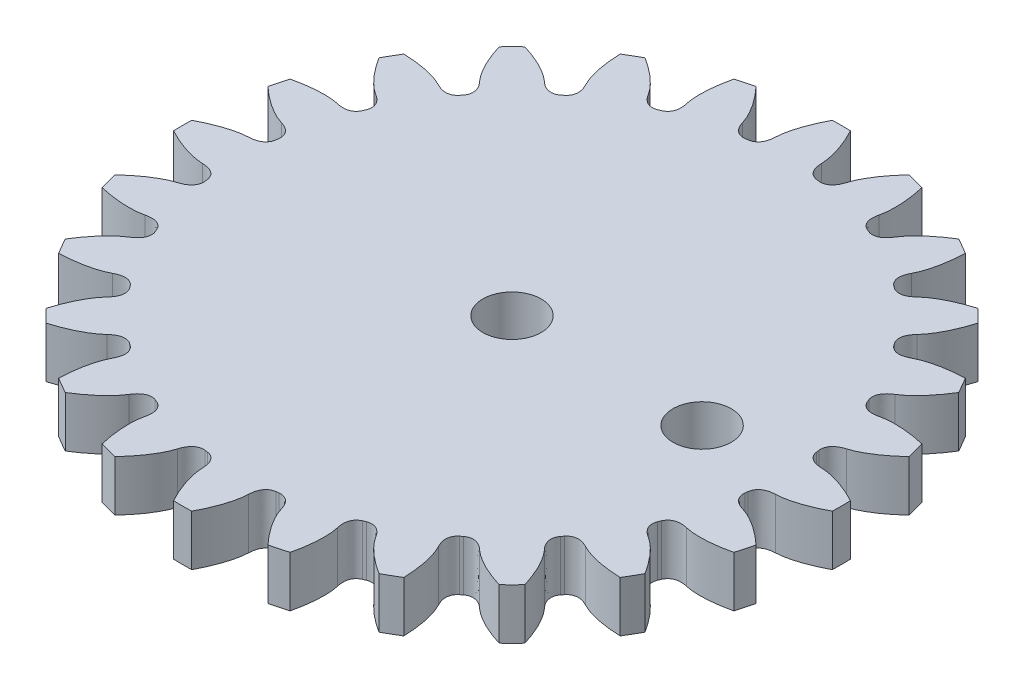
SolidWorks part; units mm, degrees
ref_plane "Спереди" through (0, 0, 0) normal (0, 0, 1) x (1, 0, 0)
ref_plane "Сверху" through (0, 0, 0) normal (0, 1, 0) x (1, 0, 0)
ref_plane "Справа" through (0, 0, 0) normal (1, 0, 0) x (0, 0, -1)
sketch "Эскиз1" plane through (0, 0, 0) normal (0, 1, 0) x (1, 0, 0)
  line L0 (0, 0) -> (7.5, 0) construction
  circle A0 centre (0, 0) radius 1.15
  circle A2 centre (7.5, 0) radius 1.15
  line B0 (-14.3, 0) -> (14.3, 0) construction
  line B1 (0, -14.3) -> (0, 14.3) construction
  arc B2 (0.3577, 12.9951) -> (-0.3577, 12.9951) centre (0, 0) ccw
  arc B3 (-1.346, 10.6654) -> (-1.4603, 10.6504) centre (0, 0) ccw
  arc B4 (-3.0178, 12.6449) -> (-3.7089, 12.4597) centre (0, 0) ccw
  arc B5 (-4.0605, 9.9536) -> (-4.1671, 9.9095) centre (0, 0) ccw
  arc B6 (-6.1877, 11.4329) -> (-6.8073, 11.0752) centre (0, 0) ccw
  arc B7 (-6.4984, 8.5635) -> (-6.5898, 8.4933) centre (0, 0) ccw
  arc B8 (-8.936, 9.4419) -> (-9.4419, 8.936) centre (0, 0) ccw
  arc B9 (-8.4933, 6.5898) -> (-8.5635, 6.4984) centre (0, 0) ccw
  arc B10 (-11.0752, 6.8073) -> (-11.4329, 6.1877) centre (0, 0) ccw
  arc B11 (-9.9095, 4.1671) -> (-9.9536, 4.0605) centre (0, 0) ccw
  arc B12 (-12.4597, 3.7089) -> (-12.6449, 3.0178) centre (0, 0) ccw
  arc B13 (-10.6504, 1.4603) -> (-10.6654, 1.346) centre (0, 0) ccw
  arc B14 (-12.9951, 0.3577) -> (-12.9951, -0.3577) centre (0, 0) ccw
  arc B15 (-10.6654, -1.346) -> (-10.6504, -1.4603) centre (0, 0) ccw
  arc B16 (-12.6449, -3.0178) -> (-12.4597, -3.7089) centre (0, 0) ccw
  arc B17 (-9.9536, -4.0605) -> (-9.9095, -4.1671) centre (0, 0) ccw
  arc B18 (-11.4329, -6.1877) -> (-11.0752, -6.8073) centre (0, 0) ccw
  arc B19 (-8.5635, -6.4984) -> (-8.4933, -6.5898) centre (0, 0) ccw
  arc B20 (-9.4419, -8.936) -> (-8.936, -9.4419) centre (0, 0) ccw
  arc B21 (-6.5898, -8.4933) -> (-6.4984, -8.5635) centre (0, 0) ccw
  arc B22 (-6.8073, -11.0752) -> (-6.1877, -11.4329) centre (0, 0) ccw
  arc B23 (-4.1671, -9.9095) -> (-4.0605, -9.9536) centre (0, 0) ccw
  arc B24 (-3.7089, -12.4597) -> (-3.0178, -12.6449) centre (0, 0) ccw
  arc B25 (-1.4603, -10.6504) -> (-1.346, -10.6654) centre (0, 0) ccw
  arc B26 (-0.3577, -12.9951) -> (0.3577, -12.9951) centre (0, 0) ccw
  arc B27 (1.346, -10.6654) -> (1.4603, -10.6504) centre (0, 0) ccw
  arc B28 (3.0178, -12.6449) -> (3.7089, -12.4597) centre (0, 0) ccw
  arc B29 (4.0605, -9.9536) -> (4.1671, -9.9095) centre (0, 0) ccw
  arc B30 (6.1877, -11.4329) -> (6.8073, -11.0752) centre (0, 0) ccw
  arc B31 (6.4984, -8.5635) -> (6.5898, -8.4933) centre (0, 0) ccw
  arc B32 (8.936, -9.4419) -> (9.4419, -8.936) centre (0, 0) ccw
  arc B33 (8.4933, -6.5898) -> (8.5635, -6.4984) centre (0, 0) ccw
  arc B34 (11.0752, -6.8073) -> (11.4329, -6.1877) centre (0, 0) ccw
  arc B35 (9.9095, -4.1671) -> (9.9536, -4.0605) centre (0, 0) ccw
  arc B36 (12.4597, -3.7089) -> (12.6449, -3.0178) centre (0, 0) ccw
  arc B37 (10.6504, -1.4603) -> (10.6654, -1.346) centre (0, 0) ccw
  arc B38 (12.9951, -0.3577) -> (12.9951, 0.3577) centre (0, 0) ccw
  arc B39 (10.6654, 1.346) -> (10.6504, 1.4603) centre (0, 0) ccw
  arc B40 (12.6449, 3.0178) -> (12.4597, 3.7089) centre (0, 0) ccw
  arc B41 (9.9536, 4.0605) -> (9.9095, 4.1671) centre (0, 0) ccw
  arc B42 (11.4329, 6.1877) -> (11.0752, 6.8073) centre (0, 0) ccw
  arc B43 (8.5635, 6.4984) -> (8.4933, 6.5898) centre (0, 0) ccw
  arc B44 (9.4419, 8.936) -> (8.936, 9.4419) centre (0, 0) ccw
  arc B45 (6.5898, 8.4933) -> (6.4984, 8.5635) centre (0, 0) ccw
  arc B46 (6.8073, 11.0752) -> (6.1877, 11.4329) centre (0, 0) ccw
  arc B47 (4.1671, 9.9095) -> (4.0605, 9.9536) centre (0, 0) ccw
  arc B48 (3.7089, 12.4597) -> (3.0178, 12.6449) centre (0, 0) ccw
  arc B49 (1.4603, 10.6504) -> (1.346, 10.6654) centre (0, 0) ccw
  circle B50 centre (0, 0) radius 12 construction
  spline B51 degree 3 poles (0.9058, 11.3017) (0.9058, 11.2304) (0.9138, 11.1608) (0.9299, 11.0929) (0.9396, 11.0522) (0.9513, 11.0113) (0.9676, 10.9727) (0.9799, 10.9437) (0.994, 10.915) (1.0107, 10.8883) (1.0248, 10.8656) (1.0406, 10.8436) (1.058, 10.8234) (1.0738, 10.805) (1.091, 10.7875) (1.1093, 10.7717) (1.1266, 10.7569) (1.1451, 10.7431) (1.1643, 10.7309) (1.1829, 10.7192) (1.2025, 10.7087) (1.2225, 10.6998) (1.2421, 10.6911) (1.2626, 10.6838) (1.2833, 10.678) (1.3038, 10.6723) (1.3247, 10.6681) (1.346, 10.6654) knots 0 0 0 0 1 1 1 2 2 2 3 3 3 4 4 4 5 5 5 6 6 6 7 7 7 8 8 8 9 9 9 9
  spline B52 degree 3 poles (-0.9058, 11.3017) (-0.9058, 11.2304) (-0.9138, 11.1608) (-0.9299, 11.0929) (-0.9396, 11.0522) (-0.9513, 11.0113) (-0.9676, 10.9727) (-0.9799, 10.9437) (-0.994, 10.915) (-1.0107, 10.8883) (-1.0248, 10.8656) (-1.0406, 10.8436) (-1.058, 10.8234) (-1.0738, 10.805) (-1.091, 10.7875) (-1.1093, 10.7717) (-1.1266, 10.7569) (-1.1451, 10.7431) (-1.1643, 10.7309) (-1.1829, 10.7192) (-1.2025, 10.7087) (-1.2225, 10.6998) (-1.2421, 10.6911) (-1.2626, 10.6838) (-1.2833, 10.678) (-1.3038, 10.6723) (-1.3247, 10.6681) (-1.346, 10.6654) knots 0 0 0 0 1 1 1 2 2 2 3 3 3 4 4 4 5 5 5 6 6 6 7 7 7 8 8 8 9 9 9 9
  spline B53 degree 3 poles (0.9058, 11.3017) (0.9032, 11.3642) (0.898, 11.4263) (0.8903, 11.4882) (0.8824, 11.551) (0.8712, 11.6136) (0.8589, 11.6757) (0.8463, 11.7389) (0.8314, 11.8016) (0.8153, 11.864) (0.7989, 11.9273) (0.7806, 11.9902) (0.7612, 12.0526) (0.7414, 12.116) (0.72, 12.179) (0.6975, 12.2415) (0.6746, 12.3049) (0.6503, 12.3678) (0.6249, 12.4303) (0.5991, 12.4937) (0.572, 12.5566) (0.5439, 12.6189) (0.5153, 12.6822) (0.4855, 12.745) (0.4547, 12.8073) (0.4235, 12.8704) (0.3912, 12.933) (0.3577, 12.9951) knots 0 0 0 0 1 1 1 2 2 2 3 3 3 4 4 4 5 5 5 6 6 6 7 7 7 8 8 8 9 9 9 9
  spline B54 degree 3 poles (-0.9058, 11.3017) (-0.9032, 11.3642) (-0.898, 11.4263) (-0.8903, 11.4882) (-0.8824, 11.551) (-0.8712, 11.6136) (-0.8589, 11.6757) (-0.8463, 11.7389) (-0.8314, 11.8016) (-0.8153, 11.864) (-0.7989, 11.9273) (-0.7806, 11.9902) (-0.7612, 12.0526) (-0.7414, 12.116) (-0.72, 12.179) (-0.6975, 12.2415) (-0.6746, 12.3049) (-0.6503, 12.3678) (-0.6249, 12.4303) (-0.5991, 12.4937) (-0.572, 12.5566) (-0.5439, 12.6189) (-0.5153, 12.6822) (-0.4855, 12.745) (-0.4547, 12.8073) (-0.4235, 12.8704) (-0.3912, 12.933) (-0.3577, 12.9951) knots 0 0 0 0 1 1 1 2 2 2 3 3 3 4 4 4 5 5 5 6 6 6 7 7 7 8 8 8 9 9 9 9
  spline B55 degree 3 poles (-2.0502, 11.151) (-2.0317, 11.0822) (-2.0059, 11.017) (-1.9728, 10.9556) (-1.9529, 10.9188) (-1.931, 10.8823) (-1.9053, 10.8493) (-1.886, 10.8244) (-1.8649, 10.8004) (-1.8419, 10.7789) (-1.8224, 10.7606) (-1.8014, 10.7435) (-1.7793, 10.7284) (-1.7594, 10.7148) (-1.7382, 10.7023) (-1.7164, 10.6918) (-1.6959, 10.6819) (-1.6745, 10.6734) (-1.6527, 10.6666) (-1.6318, 10.6601) (-1.6101, 10.655) (-1.5885, 10.6516) (-1.5672, 10.6483) (-1.5456, 10.6465) (-1.5241, 10.6463) (-1.5028, 10.6461) (-1.4816, 10.6475) (-1.4603, 10.6504) knots 0 0 0 0 1 1 1 2 2 2 3 3 3 4 4 4 5 5 5 6 6 6 7 7 7 8 8 8 9 9 9 9
  spline B56 degree 3 poles (-3.8, 10.6822) (-3.7815, 10.6133) (-3.7713, 10.544) (-3.7693, 10.4743) (-3.7681, 10.4325) (-3.7688, 10.3898) (-3.7746, 10.3484) (-3.7789, 10.3172) (-3.7852, 10.2858) (-3.7943, 10.2557) (-3.8021, 10.2302) (-3.8117, 10.2048) (-3.8232, 10.1807) (-3.8337, 10.1589) (-3.8458, 10.1376) (-3.8595, 10.1176) (-3.8723, 10.0988) (-3.8866, 10.0806) (-3.902, 10.0639) (-3.9169, 10.0478) (-3.9331, 10.0326) (-3.9502, 10.0188) (-3.9669, 10.0053) (-3.9848, 9.9929) (-4.0032, 9.982) (-4.0216, 9.9712) (-4.0406, 9.9618) (-4.0605, 9.9536) knots 0 0 0 0 1 1 1 2 2 2 3 3 3 4 4 4 5 5 5 6 6 6 7 7 7 8 8 8 9 9 9 9
  spline B57 degree 3 poles (-2.0502, 11.151) (-2.0689, 11.2107) (-2.09, 11.2694) (-2.1134, 11.3271) (-2.1373, 11.3858) (-2.1643, 11.4434) (-2.1923, 11.5002) (-2.2208, 11.5579) (-2.2514, 11.6147) (-2.2831, 11.6707) (-2.3153, 11.7276) (-2.3493, 11.7837) (-2.3842, 11.8389) (-2.4197, 11.8951) (-2.4567, 11.9503) (-2.4946, 12.0049) (-2.5331, 12.0602) (-2.5729, 12.1147) (-2.6136, 12.1685) (-2.6549, 12.223) (-2.6974, 12.2768) (-2.7407, 12.3297) (-2.7847, 12.3835) (-2.8297, 12.4364) (-2.8755, 12.4885) (-2.9221, 12.5415) (-2.9695, 12.5936) (-3.0178, 12.6449) knots 0 0 0 0 1 1 1 2 2 2 3 3 3 4 4 4 5 5 5 6 6 6 7 7 7 8 8 8 9 9 9 9
  spline B58 degree 3 poles (-3.8, 10.6822) (-3.8136, 10.7432) (-3.8247, 10.8046) (-3.8333, 10.8663) (-3.842, 10.929) (-3.8474, 10.9924) (-3.8515, 11.0556) (-3.8557, 11.1198) (-3.8576, 11.1843) (-3.8581, 11.2487) (-3.8587, 11.3141) (-3.8573, 11.3796) (-3.8547, 11.4449) (-3.852, 11.5113) (-3.8476, 11.5776) (-3.8421, 11.6438) (-3.8364, 11.711) (-3.8292, 11.7781) (-3.8208, 11.845) (-3.8123, 11.9129) (-3.8024, 11.9807) (-3.7914, 12.0482) (-3.7802, 12.1167) (-3.7676, 12.1851) (-3.754, 12.2532) (-3.7402, 12.3223) (-3.7251, 12.3911) (-3.7089, 12.4597) knots 0 0 0 0 1 1 1 2 2 2 3 3 3 4 4 4 5 5 5 6 6 6 7 7 7 8 8 8 9 9 9 9
  spline B59 degree 3 poles (-4.8664, 10.2404) (-4.8308, 10.1787) (-4.789, 10.1225) (-4.7411, 10.0717) (-4.7124, 10.0413) (-4.6817, 10.0117) (-4.6484, 9.9865) (-4.6233, 9.9675) (-4.5967, 9.9497) (-4.5689, 9.9349) (-4.5453, 9.9223) (-4.5206, 9.9111) (-4.4954, 9.9023) (-4.4726, 9.8943) (-4.4489, 9.8878) (-4.4252, 9.8833) (-4.4028, 9.879) (-4.3799, 9.8763) (-4.3571, 9.8754) (-4.3352, 9.8745) (-4.313, 9.8752) (-4.2912, 9.8776) (-4.2698, 9.8798) (-4.2484, 9.8837) (-4.2276, 9.8891) (-4.2071, 9.8944) (-4.1869, 9.9012) (-4.1671, 9.9095) knots 0 0 0 0 1 1 1 2 2 2 3 3 3 4 4 4 5 5 5 6 6 6 7 7 7 8 8 8 9 9 9 9
  spline B60 degree 3 poles (-6.4353, 9.3347) (-6.3996, 9.2729) (-6.3718, 9.2086) (-6.3518, 9.1418) (-6.3398, 9.1017) (-6.3295, 9.0604) (-6.3243, 9.0188) (-6.3204, 8.9876) (-6.3184, 8.9557) (-6.3194, 8.9242) (-6.3203, 8.8975) (-6.323, 8.8706) (-6.3279, 8.8443) (-6.3324, 8.8205) (-6.3386, 8.7968) (-6.3466, 8.7739) (-6.3541, 8.7524) (-6.3632, 8.7312) (-6.3738, 8.7111) (-6.384, 8.6917) (-6.3957, 8.6728) (-6.4086, 8.655) (-6.4213, 8.6377) (-6.4353, 8.6211) (-6.4504, 8.6058) (-6.4653, 8.5906) (-6.4813, 8.5765) (-6.4984, 8.5635) knots 0 0 0 0 1 1 1 2 2 2 3 3 3 4 4 4 5 5 5 6 6 6 7 7 7 8 8 8 9 9 9 9
  spline B61 degree 3 poles (-4.8664, 10.2404) (-4.8999, 10.2932) (-4.9355, 10.3445) (-4.9731, 10.3942) (-5.0113, 10.4447) (-5.0523, 10.4933) (-5.0941, 10.5409) (-5.1365, 10.5893) (-5.1808, 10.6362) (-5.2259, 10.6822) (-5.2718, 10.7288) (-5.319, 10.7741) (-5.3671, 10.8185) (-5.4159, 10.8635) (-5.4659, 10.9073) (-5.5167, 10.9502) (-5.5682, 10.9937) (-5.6207, 11.036) (-5.674, 11.0774) (-5.728, 11.1194) (-5.7829, 11.1603) (-5.8385, 11.2003) (-5.8949, 11.2408) (-5.9521, 11.2803) (-6.0098, 11.3188) (-6.0685, 11.3578) (-6.1278, 11.3959) (-6.1877, 11.4329) knots 0 0 0 0 1 1 1 2 2 2 3 3 3 4 4 4 5 5 5 6 6 6 7 7 7 8 8 8 9 9 9 9
  spline B62 degree 3 poles (-6.4353, 9.3347) (-6.4642, 9.3901) (-6.4908, 9.4465) (-6.5151, 9.5039) (-6.5397, 9.5623) (-6.5613, 9.622) (-6.5817, 9.6821) (-6.6024, 9.743) (-6.6209, 9.8048) (-6.638, 9.8669) (-6.6555, 9.9299) (-6.6711, 9.9935) (-6.6855, 10.0573) (-6.7001, 10.1221) (-6.713, 10.1873) (-6.7248, 10.2527) (-6.7367, 10.319) (-6.7471, 10.3857) (-6.7563, 10.4525) (-6.7657, 10.5203) (-6.7737, 10.5883) (-6.7805, 10.6564) (-6.7874, 10.7255) (-6.793, 10.7948) (-6.7974, 10.8641) (-6.8019, 10.9344) (-6.8053, 11.0047) (-6.8073, 11.0752) knots 0 0 0 0 1 1 1 2 2 2 3 3 3 4 4 4 5 5 5 6 6 6 7 7 7 8 8 8 9 9 9 9
  spline B63 degree 3 poles (-7.351, 8.632) (-7.3006, 8.5816) (-7.2457, 8.5381) (-7.1863, 8.5015) (-7.1507, 8.4795) (-7.1134, 8.4588) (-7.0747, 8.4431) (-7.0455, 8.4312) (-7.0152, 8.421) (-6.9845, 8.4138) (-6.9585, 8.4078) (-6.9318, 8.4034) (-6.9052, 8.4014) (-6.881, 8.3996) (-6.8565, 8.3994) (-6.8324, 8.4012) (-6.8097, 8.4029) (-6.7868, 8.4062) (-6.7646, 8.4112) (-6.7432, 8.416) (-6.7219, 8.4224) (-6.7015, 8.4304) (-6.6814, 8.4381) (-6.6618, 8.4474) (-6.6431, 8.4579) (-6.6246, 8.4684) (-6.6068, 8.4802) (-6.5898, 8.4933) knots 0 0 0 0 1 1 1 2 2 2 3 3 3 4 4 4 5 5 5 6 6 6 7 7 7 8 8 8 9 9 9 9
  spline B64 degree 3 poles (-8.632, 7.351) (-8.5816, 7.3006) (-8.5381, 7.2457) (-8.5015, 7.1863) (-8.4795, 7.1507) (-8.4588, 7.1134) (-8.4431, 7.0747) (-8.4312, 7.0455) (-8.421, 7.0152) (-8.4138, 6.9845) (-8.4078, 6.9585) (-8.4034, 6.9318) (-8.4014, 6.9052) (-8.3996, 6.881) (-8.3994, 6.8565) (-8.4012, 6.8324) (-8.4029, 6.8097) (-8.4062, 6.7868) (-8.4112, 6.7646) (-8.416, 6.7432) (-8.4224, 6.7219) (-8.4304, 6.7015) (-8.4381, 6.6814) (-8.4474, 6.6618) (-8.4579, 6.6431) (-8.4684, 6.6246) (-8.4802, 6.6068) (-8.4933, 6.5898) knots 0 0 0 0 1 1 1 2 2 2 3 3 3 4 4 4 5 5 5 6 6 6 7 7 7 8 8 8 9 9 9 9
  spline B65 degree 3 poles (-7.351, 8.632) (-7.3971, 8.6743) (-7.4447, 8.7146) (-7.4938, 8.7529) (-7.5438, 8.7918) (-7.596, 8.8281) (-7.6487, 8.8633) (-7.7022, 8.8991) (-7.7571, 8.9329) (-7.8126, 8.9656) (-7.869, 8.9988) (-7.9263, 9.0303) (-7.9843, 9.0607) (-8.0431, 9.0916) (-8.1027, 9.121) (-8.1628, 9.1492) (-8.2238, 9.1779) (-8.2855, 9.2052) (-8.3477, 9.2314) (-8.4107, 9.258) (-8.4744, 9.2833) (-8.5384, 9.3075) (-8.6033, 9.3321) (-8.6688, 9.3554) (-8.7346, 9.3776) (-8.8013, 9.4002) (-8.8684, 9.4216) (-8.936, 9.4419) knots 0 0 0 0 1 1 1 2 2 2 3 3 3 4 4 4 5 5 5 6 6 6 7 7 7 8 8 8 9 9 9 9
  spline B66 degree 3 poles (-8.632, 7.351) (-8.6743, 7.3971) (-8.7146, 7.4447) (-8.7529, 7.4938) (-8.7918, 7.5438) (-8.8281, 7.596) (-8.8633, 7.6487) (-8.8991, 7.7022) (-8.9329, 7.7571) (-8.9656, 7.8126) (-8.9988, 7.869) (-9.0303, 7.9263) (-9.0607, 7.9843) (-9.0916, 8.0431) (-9.121, 8.1027) (-9.1492, 8.1628) (-9.1779, 8.2238) (-9.2052, 8.2855) (-9.2314, 8.3477) (-9.258, 8.4107) (-9.2833, 8.4744) (-9.3075, 8.5384) (-9.3321, 8.6033) (-9.3554, 8.6688) (-9.3776, 8.7346) (-9.4002, 8.8013) (-9.4216, 8.8684) (-9.4419, 8.936) knots 0 0 0 0 1 1 1 2 2 2 3 3 3 4 4 4 5 5 5 6 6 6 7 7 7 8 8 8 9 9 9 9
  spline B67 degree 3 poles (-9.3347, 6.4353) (-9.2729, 6.3996) (-9.2086, 6.3718) (-9.1418, 6.3518) (-9.1017, 6.3398) (-9.0604, 6.3295) (-9.0188, 6.3243) (-8.9876, 6.3204) (-8.9557, 6.3184) (-8.9242, 6.3194) (-8.8975, 6.3203) (-8.8706, 6.323) (-8.8443, 6.3279) (-8.8205, 6.3324) (-8.7968, 6.3386) (-8.7739, 6.3466) (-8.7524, 6.3541) (-8.7312, 6.3632) (-8.7111, 6.3738) (-8.6917, 6.384) (-8.6728, 6.3957) (-8.655, 6.4086) (-8.6377, 6.4213) (-8.6211, 6.4353) (-8.6058, 6.4504) (-8.5906, 6.4653) (-8.5765, 6.4813) (-8.5635, 6.4984) knots 0 0 0 0 1 1 1 2 2 2 3 3 3 4 4 4 5 5 5 6 6 6 7 7 7 8 8 8 9 9 9 9
  spline B68 degree 3 poles (-10.2404, 4.8664) (-10.1787, 4.8308) (-10.1225, 4.789) (-10.0717, 4.7411) (-10.0413, 4.7124) (-10.0117, 4.6817) (-9.9865, 4.6484) (-9.9675, 4.6233) (-9.9497, 4.5967) (-9.9349, 4.5689) (-9.9223, 4.5453) (-9.9111, 4.5206) (-9.9023, 4.4954) (-9.8943, 4.4726) (-9.8878, 4.4489) (-9.8833, 4.4252) (-9.879, 4.4028) (-9.8763, 4.3799) (-9.8754, 4.3571) (-9.8745, 4.3352) (-9.8752, 4.313) (-9.8776, 4.2912) (-9.8798, 4.2698) (-9.8837, 4.2484) (-9.8891, 4.2276) (-9.8944, 4.2071) (-9.9012, 4.1869) (-9.9095, 4.1671) knots 0 0 0 0 1 1 1 2 2 2 3 3 3 4 4 4 5 5 5 6 6 6 7 7 7 8 8 8 9 9 9 9
  spline B69 degree 3 poles (-9.3347, 6.4353) (-9.3901, 6.4642) (-9.4465, 6.4908) (-9.5039, 6.5151) (-9.5623, 6.5397) (-9.622, 6.5613) (-9.6821, 6.5817) (-9.743, 6.6024) (-9.8048, 6.6209) (-9.8669, 6.638) (-9.9299, 6.6555) (-9.9935, 6.6711) (-10.0573, 6.6855) (-10.1221, 6.7001) (-10.1873, 6.713) (-10.2527, 6.7248) (-10.319, 6.7367) (-10.3857, 6.7471) (-10.4525, 6.7563) (-10.5203, 6.7657) (-10.5883, 6.7737) (-10.6564, 6.7805) (-10.7255, 6.7874) (-10.7948, 6.793) (-10.8641, 6.7974) (-10.9344, 6.8019) (-11.0047, 6.8053) (-11.0752, 6.8073) knots 0 0 0 0 1 1 1 2 2 2 3 3 3 4 4 4 5 5 5 6 6 6 7 7 7 8 8 8 9 9 9 9
  spline B70 degree 3 poles (-10.2404, 4.8664) (-10.2932, 4.8999) (-10.3445, 4.9355) (-10.3942, 4.9731) (-10.4447, 5.0113) (-10.4933, 5.0523) (-10.5409, 5.0941) (-10.5893, 5.1365) (-10.6362, 5.1808) (-10.6822, 5.2259) (-10.7288, 5.2718) (-10.7741, 5.319) (-10.8185, 5.3671) (-10.8635, 5.4159) (-10.9073, 5.4659) (-10.9502, 5.5167) (-10.9937, 5.5682) (-11.036, 5.6207) (-11.0774, 5.674) (-11.1194, 5.728) (-11.1603, 5.7829) (-11.2003, 5.8385) (-11.2408, 5.8949) (-11.2803, 5.9521) (-11.3188, 6.0098) (-11.3578, 6.0685) (-11.3959, 6.1278) (-11.4329, 6.1877) knots 0 0 0 0 1 1 1 2 2 2 3 3 3 4 4 4 5 5 5 6 6 6 7 7 7 8 8 8 9 9 9 9
  spline B71 degree 3 poles (-10.6822, 3.8) (-10.6133, 3.7815) (-10.544, 3.7713) (-10.4743, 3.7693) (-10.4325, 3.7681) (-10.3898, 3.7688) (-10.3484, 3.7746) (-10.3172, 3.7789) (-10.2858, 3.7852) (-10.2557, 3.7943) (-10.2302, 3.8021) (-10.2048, 3.8117) (-10.1807, 3.8232) (-10.1589, 3.8337) (-10.1376, 3.8458) (-10.1176, 3.8595) (-10.0988, 3.8723) (-10.0806, 3.8866) (-10.0639, 3.902) (-10.0478, 3.9169) (-10.0326, 3.9331) (-10.0188, 3.9502) (-10.0053, 3.9669) (-9.9929, 3.9848) (-9.982, 4.0032) (-9.9712, 4.0216) (-9.9618, 4.0406) (-9.9536, 4.0605) knots 0 0 0 0 1 1 1 2 2 2 3 3 3 4 4 4 5 5 5 6 6 6 7 7 7 8 8 8 9 9 9 9
  spline B72 degree 3 poles (-11.151, 2.0502) (-11.0822, 2.0317) (-11.017, 2.0059) (-10.9556, 1.9728) (-10.9188, 1.9529) (-10.8823, 1.931) (-10.8493, 1.9053) (-10.8244, 1.886) (-10.8004, 1.8649) (-10.7789, 1.8419) (-10.7606, 1.8224) (-10.7435, 1.8014) (-10.7284, 1.7793) (-10.7148, 1.7594) (-10.7023, 1.7382) (-10.6918, 1.7164) (-10.6819, 1.6959) (-10.6734, 1.6745) (-10.6666, 1.6527) (-10.6601, 1.6318) (-10.655, 1.6101) (-10.6516, 1.5885) (-10.6483, 1.5672) (-10.6465, 1.5456) (-10.6463, 1.5241) (-10.6461, 1.5028) (-10.6475, 1.4816) (-10.6504, 1.4603) knots 0 0 0 0 1 1 1 2 2 2 3 3 3 4 4 4 5 5 5 6 6 6 7 7 7 8 8 8 9 9 9 9
  spline B73 degree 3 poles (-10.6822, 3.8) (-10.7432, 3.8136) (-10.8046, 3.8247) (-10.8663, 3.8333) (-10.929, 3.842) (-10.9924, 3.8474) (-11.0556, 3.8515) (-11.1198, 3.8557) (-11.1843, 3.8576) (-11.2487, 3.8581) (-11.3141, 3.8587) (-11.3796, 3.8573) (-11.4449, 3.8547) (-11.5113, 3.852) (-11.5776, 3.8476) (-11.6438, 3.8421) (-11.711, 3.8364) (-11.7781, 3.8292) (-11.845, 3.8208) (-11.9129, 3.8123) (-11.9807, 3.8024) (-12.0482, 3.7914) (-12.1167, 3.7802) (-12.1851, 3.7676) (-12.2532, 3.754) (-12.3223, 3.7402) (-12.3911, 3.7251) (-12.4597, 3.7089) knots 0 0 0 0 1 1 1 2 2 2 3 3 3 4 4 4 5 5 5 6 6 6 7 7 7 8 8 8 9 9 9 9
  spline B74 degree 3 poles (-11.151, 2.0502) (-11.2107, 2.0689) (-11.2694, 2.09) (-11.3271, 2.1134) (-11.3858, 2.1373) (-11.4434, 2.1643) (-11.5002, 2.1923) (-11.5579, 2.2208) (-11.6147, 2.2514) (-11.6707, 2.2831) (-11.7276, 2.3153) (-11.7837, 2.3493) (-11.8389, 2.3842) (-11.8951, 2.4197) (-11.9503, 2.4567) (-12.0049, 2.4946) (-12.0602, 2.5331) (-12.1147, 2.5729) (-12.1685, 2.6136) (-12.223, 2.6549) (-12.2768, 2.6974) (-12.3297, 2.7407) (-12.3835, 2.7847) (-12.4364, 2.8297) (-12.4885, 2.8755) (-12.5415, 2.9221) (-12.5936, 2.9695) (-12.6449, 3.0178) knots 0 0 0 0 1 1 1 2 2 2 3 3 3 4 4 4 5 5 5 6 6 6 7 7 7 8 8 8 9 9 9 9
  spline B75 degree 3 poles (-11.3017, 0.9058) (-11.2304, 0.9058) (-11.1608, 0.9138) (-11.0929, 0.9299) (-11.0522, 0.9396) (-11.0113, 0.9513) (-10.9727, 0.9676) (-10.9437, 0.9799) (-10.915, 0.994) (-10.8883, 1.0107) (-10.8656, 1.0248) (-10.8436, 1.0406) (-10.8234, 1.058) (-10.805, 1.0738) (-10.7875, 1.091) (-10.7717, 1.1093) (-10.7569, 1.1266) (-10.7431, 1.1451) (-10.7309, 1.1643) (-10.7192, 1.1829) (-10.7087, 1.2025) (-10.6998, 1.2225) (-10.6911, 1.2421) (-10.6838, 1.2626) (-10.678, 1.2833) (-10.6723, 1.3038) (-10.6681, 1.3247) (-10.6654, 1.346) knots 0 0 0 0 1 1 1 2 2 2 3 3 3 4 4 4 5 5 5 6 6 6 7 7 7 8 8 8 9 9 9 9
  spline B76 degree 3 poles (-11.3017, -0.9058) (-11.2304, -0.9058) (-11.1608, -0.9138) (-11.0929, -0.9299) (-11.0522, -0.9396) (-11.0113, -0.9513) (-10.9727, -0.9676) (-10.9437, -0.9799) (-10.915, -0.994) (-10.8883, -1.0107) (-10.8656, -1.0248) (-10.8436, -1.0406) (-10.8234, -1.058) (-10.805, -1.0738) (-10.7875, -1.091) (-10.7717, -1.1093) (-10.7569, -1.1266) (-10.7431, -1.1451) (-10.7309, -1.1643) (-10.7192, -1.1829) (-10.7087, -1.2025) (-10.6998, -1.2225) (-10.6911, -1.2421) (-10.6838, -1.2626) (-10.678, -1.2833) (-10.6723, -1.3038) (-10.6681, -1.3247) (-10.6654, -1.346) knots 0 0 0 0 1 1 1 2 2 2 3 3 3 4 4 4 5 5 5 6 6 6 7 7 7 8 8 8 9 9 9 9
  spline B77 degree 3 poles (-11.3017, 0.9058) (-11.3642, 0.9032) (-11.4263, 0.898) (-11.4882, 0.8903) (-11.551, 0.8824) (-11.6136, 0.8712) (-11.6757, 0.8589) (-11.7389, 0.8463) (-11.8016, 0.8314) (-11.864, 0.8153) (-11.9273, 0.7989) (-11.9902, 0.7806) (-12.0526, 0.7612) (-12.116, 0.7414) (-12.179, 0.72) (-12.2415, 0.6975) (-12.3049, 0.6746) (-12.3678, 0.6503) (-12.4303, 0.6249) (-12.4937, 0.5991) (-12.5566, 0.572) (-12.6189, 0.5439) (-12.6822, 0.5153) (-12.745, 0.4855) (-12.8073, 0.4547) (-12.8704, 0.4235) (-12.933, 0.3912) (-12.9951, 0.3577) knots 0 0 0 0 1 1 1 2 2 2 3 3 3 4 4 4 5 5 5 6 6 6 7 7 7 8 8 8 9 9 9 9
  spline B78 degree 3 poles (-11.3017, -0.9058) (-11.3642, -0.9032) (-11.4263, -0.898) (-11.4882, -0.8903) (-11.551, -0.8824) (-11.6136, -0.8712) (-11.6757, -0.8589) (-11.7389, -0.8463) (-11.8016, -0.8314) (-11.864, -0.8153) (-11.9273, -0.7989) (-11.9902, -0.7806) (-12.0526, -0.7612) (-12.116, -0.7414) (-12.179, -0.72) (-12.2415, -0.6975) (-12.3049, -0.6746) (-12.3678, -0.6503) (-12.4303, -0.6249) (-12.4937, -0.5991) (-12.5566, -0.572) (-12.6189, -0.5439) (-12.6822, -0.5153) (-12.745, -0.4855) (-12.8073, -0.4547) (-12.8704, -0.4235) (-12.933, -0.3912) (-12.9951, -0.3577) knots 0 0 0 0 1 1 1 2 2 2 3 3 3 4 4 4 5 5 5 6 6 6 7 7 7 8 8 8 9 9 9 9
  spline B79 degree 3 poles (-11.151, -2.0502) (-11.0822, -2.0317) (-11.017, -2.0059) (-10.9556, -1.9728) (-10.9188, -1.9529) (-10.8823, -1.931) (-10.8493, -1.9053) (-10.8244, -1.886) (-10.8004, -1.8649) (-10.7789, -1.8419) (-10.7606, -1.8224) (-10.7435, -1.8014) (-10.7284, -1.7793) (-10.7148, -1.7594) (-10.7023, -1.7382) (-10.6918, -1.7164) (-10.6819, -1.6959) (-10.6734, -1.6745) (-10.6666, -1.6527) (-10.6601, -1.6318) (-10.655, -1.6101) (-10.6516, -1.5885) (-10.6483, -1.5672) (-10.6465, -1.5456) (-10.6463, -1.5241) (-10.6461, -1.5028) (-10.6475, -1.4816) (-10.6504, -1.4603) knots 0 0 0 0 1 1 1 2 2 2 3 3 3 4 4 4 5 5 5 6 6 6 7 7 7 8 8 8 9 9 9 9
  spline B80 degree 3 poles (-10.6822, -3.8) (-10.6133, -3.7815) (-10.544, -3.7713) (-10.4743, -3.7693) (-10.4325, -3.7681) (-10.3898, -3.7688) (-10.3484, -3.7746) (-10.3172, -3.7789) (-10.2858, -3.7852) (-10.2557, -3.7943) (-10.2302, -3.8021) (-10.2048, -3.8117) (-10.1807, -3.8232) (-10.1589, -3.8337) (-10.1376, -3.8458) (-10.1176, -3.8595) (-10.0988, -3.8723) (-10.0806, -3.8866) (-10.0639, -3.902) (-10.0478, -3.9169) (-10.0326, -3.9331) (-10.0188, -3.9502) (-10.0053, -3.9669) (-9.9929, -3.9848) (-9.982, -4.0032) (-9.9712, -4.0216) (-9.9618, -4.0406) (-9.9536, -4.0605) knots 0 0 0 0 1 1 1 2 2 2 3 3 3 4 4 4 5 5 5 6 6 6 7 7 7 8 8 8 9 9 9 9
  spline B81 degree 3 poles (-11.151, -2.0502) (-11.2107, -2.0689) (-11.2694, -2.09) (-11.3271, -2.1134) (-11.3858, -2.1373) (-11.4434, -2.1643) (-11.5002, -2.1923) (-11.5579, -2.2208) (-11.6147, -2.2514) (-11.6707, -2.2831) (-11.7276, -2.3153) (-11.7837, -2.3493) (-11.8389, -2.3842) (-11.8951, -2.4197) (-11.9503, -2.4567) (-12.0049, -2.4946) (-12.0602, -2.5331) (-12.1147, -2.5729) (-12.1685, -2.6136) (-12.223, -2.6549) (-12.2768, -2.6974) (-12.3297, -2.7407) (-12.3835, -2.7847) (-12.4364, -2.8297) (-12.4885, -2.8755) (-12.5415, -2.9221) (-12.5936, -2.9695) (-12.6449, -3.0178) knots 0 0 0 0 1 1 1 2 2 2 3 3 3 4 4 4 5 5 5 6 6 6 7 7 7 8 8 8 9 9 9 9
  spline B82 degree 3 poles (-10.6822, -3.8) (-10.7432, -3.8136) (-10.8046, -3.8247) (-10.8663, -3.8333) (-10.929, -3.842) (-10.9924, -3.8474) (-11.0556, -3.8515) (-11.1198, -3.8557) (-11.1843, -3.8576) (-11.2487, -3.8581) (-11.3141, -3.8587) (-11.3796, -3.8573) (-11.4449, -3.8547) (-11.5113, -3.852) (-11.5776, -3.8476) (-11.6438, -3.8421) (-11.711, -3.8364) (-11.7781, -3.8292) (-11.845, -3.8208) (-11.9129, -3.8123) (-11.9807, -3.8024) (-12.0482, -3.7914) (-12.1167, -3.7802) (-12.1851, -3.7676) (-12.2532, -3.754) (-12.3223, -3.7402) (-12.3911, -3.7251) (-12.4597, -3.7089) knots 0 0 0 0 1 1 1 2 2 2 3 3 3 4 4 4 5 5 5 6 6 6 7 7 7 8 8 8 9 9 9 9
  spline B83 degree 3 poles (-10.2404, -4.8664) (-10.1787, -4.8308) (-10.1225, -4.789) (-10.0717, -4.7411) (-10.0413, -4.7124) (-10.0117, -4.6817) (-9.9865, -4.6484) (-9.9675, -4.6233) (-9.9497, -4.5967) (-9.9349, -4.5689) (-9.9223, -4.5453) (-9.9111, -4.5206) (-9.9023, -4.4954) (-9.8943, -4.4726) (-9.8878, -4.4489) (-9.8833, -4.4252) (-9.879, -4.4028) (-9.8763, -4.3799) (-9.8754, -4.3571) (-9.8745, -4.3352) (-9.8752, -4.313) (-9.8776, -4.2912) (-9.8798, -4.2698) (-9.8837, -4.2484) (-9.8891, -4.2276) (-9.8944, -4.2071) (-9.9012, -4.1869) (-9.9095, -4.1671) knots 0 0 0 0 1 1 1 2 2 2 3 3 3 4 4 4 5 5 5 6 6 6 7 7 7 8 8 8 9 9 9 9
  spline B84 degree 3 poles (-9.3347, -6.4353) (-9.2729, -6.3996) (-9.2086, -6.3718) (-9.1418, -6.3518) (-9.1017, -6.3398) (-9.0604, -6.3295) (-9.0188, -6.3243) (-8.9876, -6.3204) (-8.9557, -6.3184) (-8.9242, -6.3194) (-8.8975, -6.3203) (-8.8706, -6.323) (-8.8443, -6.3279) (-8.8205, -6.3324) (-8.7968, -6.3386) (-8.7739, -6.3466) (-8.7524, -6.3541) (-8.7312, -6.3632) (-8.7111, -6.3738) (-8.6917, -6.384) (-8.6728, -6.3957) (-8.655, -6.4086) (-8.6377, -6.4213) (-8.6211, -6.4353) (-8.6058, -6.4504) (-8.5906, -6.4653) (-8.5765, -6.4813) (-8.5635, -6.4984) knots 0 0 0 0 1 1 1 2 2 2 3 3 3 4 4 4 5 5 5 6 6 6 7 7 7 8 8 8 9 9 9 9
  spline B85 degree 3 poles (-10.2404, -4.8664) (-10.2932, -4.8999) (-10.3445, -4.9355) (-10.3942, -4.9731) (-10.4447, -5.0113) (-10.4933, -5.0523) (-10.5409, -5.0941) (-10.5893, -5.1365) (-10.6362, -5.1808) (-10.6822, -5.2259) (-10.7288, -5.2718) (-10.7741, -5.319) (-10.8185, -5.3671) (-10.8635, -5.4159) (-10.9073, -5.4659) (-10.9502, -5.5167) (-10.9937, -5.5682) (-11.036, -5.6207) (-11.0774, -5.674) (-11.1194, -5.728) (-11.1603, -5.7829) (-11.2003, -5.8385) (-11.2408, -5.8949) (-11.2803, -5.9521) (-11.3188, -6.0098) (-11.3578, -6.0685) (-11.3959, -6.1278) (-11.4329, -6.1877) knots 0 0 0 0 1 1 1 2 2 2 3 3 3 4 4 4 5 5 5 6 6 6 7 7 7 8 8 8 9 9 9 9
  spline B86 degree 3 poles (-9.3347, -6.4353) (-9.3901, -6.4642) (-9.4465, -6.4908) (-9.5039, -6.5151) (-9.5623, -6.5397) (-9.622, -6.5613) (-9.6821, -6.5817) (-9.743, -6.6024) (-9.8048, -6.6209) (-9.8669, -6.638) (-9.9299, -6.6555) (-9.9935, -6.6711) (-10.0573, -6.6855) (-10.1221, -6.7001) (-10.1873, -6.713) (-10.2527, -6.7248) (-10.319, -6.7367) (-10.3857, -6.7471) (-10.4525, -6.7563) (-10.5203, -6.7657) (-10.5883, -6.7737) (-10.6564, -6.7805) (-10.7255, -6.7874) (-10.7948, -6.793) (-10.8641, -6.7974) (-10.9344, -6.8019) (-11.0047, -6.8053) (-11.0752, -6.8073) knots 0 0 0 0 1 1 1 2 2 2 3 3 3 4 4 4 5 5 5 6 6 6 7 7 7 8 8 8 9 9 9 9
  spline B87 degree 3 poles (-8.632, -7.351) (-8.5816, -7.3006) (-8.5381, -7.2457) (-8.5015, -7.1863) (-8.4795, -7.1507) (-8.4588, -7.1134) (-8.4431, -7.0747) (-8.4312, -7.0455) (-8.421, -7.0152) (-8.4138, -6.9845) (-8.4078, -6.9585) (-8.4034, -6.9318) (-8.4014, -6.9052) (-8.3996, -6.881) (-8.3994, -6.8565) (-8.4012, -6.8324) (-8.4029, -6.8097) (-8.4062, -6.7868) (-8.4112, -6.7646) (-8.416, -6.7432) (-8.4224, -6.7219) (-8.4304, -6.7015) (-8.4381, -6.6814) (-8.4474, -6.6618) (-8.4579, -6.6431) (-8.4684, -6.6246) (-8.4802, -6.6068) (-8.4933, -6.5898) knots 0 0 0 0 1 1 1 2 2 2 3 3 3 4 4 4 5 5 5 6 6 6 7 7 7 8 8 8 9 9 9 9
  spline B88 degree 3 poles (-7.351, -8.632) (-7.3006, -8.5816) (-7.2457, -8.5381) (-7.1863, -8.5015) (-7.1507, -8.4795) (-7.1134, -8.4588) (-7.0747, -8.4431) (-7.0455, -8.4312) (-7.0152, -8.421) (-6.9845, -8.4138) (-6.9585, -8.4078) (-6.9318, -8.4034) (-6.9052, -8.4014) (-6.881, -8.3996) (-6.8565, -8.3994) (-6.8324, -8.4012) (-6.8097, -8.4029) (-6.7868, -8.4062) (-6.7646, -8.4112) (-6.7432, -8.416) (-6.7219, -8.4224) (-6.7015, -8.4304) (-6.6814, -8.4381) (-6.6618, -8.4474) (-6.6431, -8.4579) (-6.6246, -8.4684) (-6.6068, -8.4802) (-6.5898, -8.4933) knots 0 0 0 0 1 1 1 2 2 2 3 3 3 4 4 4 5 5 5 6 6 6 7 7 7 8 8 8 9 9 9 9
  spline B89 degree 3 poles (-8.632, -7.351) (-8.6743, -7.3971) (-8.7146, -7.4447) (-8.7529, -7.4938) (-8.7918, -7.5438) (-8.8281, -7.596) (-8.8633, -7.6487) (-8.8991, -7.7022) (-8.9329, -7.7571) (-8.9656, -7.8126) (-8.9988, -7.869) (-9.0303, -7.9263) (-9.0607, -7.9843) (-9.0916, -8.0431) (-9.121, -8.1027) (-9.1492, -8.1628) (-9.1779, -8.2238) (-9.2052, -8.2855) (-9.2314, -8.3477) (-9.258, -8.4107) (-9.2833, -8.4744) (-9.3075, -8.5384) (-9.3321, -8.6033) (-9.3554, -8.6688) (-9.3776, -8.7346) (-9.4002, -8.8013) (-9.4216, -8.8684) (-9.4419, -8.936) knots 0 0 0 0 1 1 1 2 2 2 3 3 3 4 4 4 5 5 5 6 6 6 7 7 7 8 8 8 9 9 9 9
  spline B90 degree 3 poles (-7.351, -8.632) (-7.3971, -8.6743) (-7.4447, -8.7146) (-7.4938, -8.7529) (-7.5438, -8.7918) (-7.596, -8.8281) (-7.6487, -8.8633) (-7.7022, -8.8991) (-7.7571, -8.9329) (-7.8126, -8.9656) (-7.869, -8.9988) (-7.9263, -9.0303) (-7.9843, -9.0607) (-8.0431, -9.0916) (-8.1027, -9.121) (-8.1628, -9.1492) (-8.2238, -9.1779) (-8.2855, -9.2052) (-8.3477, -9.2314) (-8.4107, -9.258) (-8.4744, -9.2833) (-8.5384, -9.3075) (-8.6033, -9.3321) (-8.6688, -9.3554) (-8.7346, -9.3776) (-8.8013, -9.4002) (-8.8684, -9.4216) (-8.936, -9.4419) knots 0 0 0 0 1 1 1 2 2 2 3 3 3 4 4 4 5 5 5 6 6 6 7 7 7 8 8 8 9 9 9 9
  spline B91 degree 3 poles (-6.4353, -9.3347) (-6.3996, -9.2729) (-6.3718, -9.2086) (-6.3518, -9.1418) (-6.3398, -9.1017) (-6.3295, -9.0604) (-6.3243, -9.0188) (-6.3204, -8.9876) (-6.3184, -8.9557) (-6.3194, -8.9242) (-6.3203, -8.8975) (-6.323, -8.8706) (-6.3279, -8.8443) (-6.3324, -8.8205) (-6.3386, -8.7968) (-6.3466, -8.7739) (-6.3541, -8.7524) (-6.3632, -8.7312) (-6.3738, -8.7111) (-6.384, -8.6917) (-6.3957, -8.6728) (-6.4086, -8.655) (-6.4213, -8.6377) (-6.4353, -8.6211) (-6.4504, -8.6058) (-6.4653, -8.5906) (-6.4813, -8.5765) (-6.4984, -8.5635) knots 0 0 0 0 1 1 1 2 2 2 3 3 3 4 4 4 5 5 5 6 6 6 7 7 7 8 8 8 9 9 9 9
  spline B92 degree 3 poles (-4.8664, -10.2404) (-4.8308, -10.1787) (-4.789, -10.1225) (-4.7411, -10.0717) (-4.7124, -10.0413) (-4.6817, -10.0117) (-4.6484, -9.9865) (-4.6233, -9.9675) (-4.5967, -9.9497) (-4.5689, -9.9349) (-4.5453, -9.9223) (-4.5206, -9.9111) (-4.4954, -9.9023) (-4.4726, -9.8943) (-4.4489, -9.8878) (-4.4252, -9.8833) (-4.4028, -9.879) (-4.3799, -9.8763) (-4.3571, -9.8754) (-4.3352, -9.8745) (-4.313, -9.8752) (-4.2912, -9.8776) (-4.2698, -9.8798) (-4.2484, -9.8837) (-4.2276, -9.8891) (-4.2071, -9.8944) (-4.1869, -9.9012) (-4.1671, -9.9095) knots 0 0 0 0 1 1 1 2 2 2 3 3 3 4 4 4 5 5 5 6 6 6 7 7 7 8 8 8 9 9 9 9
  spline B93 degree 3 poles (-6.4353, -9.3347) (-6.4642, -9.3901) (-6.4908, -9.4465) (-6.5151, -9.5039) (-6.5397, -9.5623) (-6.5613, -9.622) (-6.5817, -9.6821) (-6.6024, -9.743) (-6.6209, -9.8048) (-6.638, -9.8669) (-6.6555, -9.9299) (-6.6711, -9.9935) (-6.6855, -10.0573) (-6.7001, -10.1221) (-6.713, -10.1873) (-6.7248, -10.2527) (-6.7367, -10.319) (-6.7471, -10.3857) (-6.7563, -10.4525) (-6.7657, -10.5203) (-6.7737, -10.5883) (-6.7805, -10.6564) (-6.7874, -10.7255) (-6.793, -10.7948) (-6.7974, -10.8641) (-6.8019, -10.9344) (-6.8053, -11.0047) (-6.8073, -11.0752) knots 0 0 0 0 1 1 1 2 2 2 3 3 3 4 4 4 5 5 5 6 6 6 7 7 7 8 8 8 9 9 9 9
  spline B94 degree 3 poles (-4.8664, -10.2404) (-4.8999, -10.2932) (-4.9355, -10.3445) (-4.9731, -10.3942) (-5.0113, -10.4447) (-5.0523, -10.4933) (-5.0941, -10.5409) (-5.1365, -10.5893) (-5.1808, -10.6362) (-5.2259, -10.6822) (-5.2718, -10.7288) (-5.319, -10.7741) (-5.3671, -10.8185) (-5.4159, -10.8635) (-5.4659, -10.9073) (-5.5167, -10.9502) (-5.5682, -10.9937) (-5.6207, -11.036) (-5.674, -11.0774) (-5.728, -11.1194) (-5.7829, -11.1603) (-5.8385, -11.2003) (-5.8949, -11.2408) (-5.9521, -11.2803) (-6.0098, -11.3188) (-6.0685, -11.3578) (-6.1278, -11.3959) (-6.1877, -11.4329) knots 0 0 0 0 1 1 1 2 2 2 3 3 3 4 4 4 5 5 5 6 6 6 7 7 7 8 8 8 9 9 9 9
  spline B95 degree 3 poles (-3.8, -10.6822) (-3.7815, -10.6133) (-3.7713, -10.544) (-3.7693, -10.4743) (-3.7681, -10.4325) (-3.7688, -10.3898) (-3.7746, -10.3484) (-3.7789, -10.3172) (-3.7852, -10.2858) (-3.7943, -10.2557) (-3.8021, -10.2302) (-3.8117, -10.2048) (-3.8232, -10.1807) (-3.8337, -10.1589) (-3.8458, -10.1376) (-3.8595, -10.1176) (-3.8723, -10.0988) (-3.8866, -10.0806) (-3.902, -10.0639) (-3.9169, -10.0478) (-3.9331, -10.0326) (-3.9502, -10.0188) (-3.9669, -10.0053) (-3.9848, -9.9929) (-4.0032, -9.982) (-4.0216, -9.9712) (-4.0406, -9.9618) (-4.0605, -9.9536) knots 0 0 0 0 1 1 1 2 2 2 3 3 3 4 4 4 5 5 5 6 6 6 7 7 7 8 8 8 9 9 9 9
  spline B96 degree 3 poles (-2.0502, -11.151) (-2.0317, -11.0822) (-2.0059, -11.017) (-1.9728, -10.9556) (-1.9529, -10.9188) (-1.931, -10.8823) (-1.9053, -10.8493) (-1.886, -10.8244) (-1.8649, -10.8004) (-1.8419, -10.7789) (-1.8224, -10.7606) (-1.8014, -10.7435) (-1.7793, -10.7284) (-1.7594, -10.7148) (-1.7382, -10.7023) (-1.7164, -10.6918) (-1.6959, -10.6819) (-1.6745, -10.6734) (-1.6527, -10.6666) (-1.6318, -10.6601) (-1.6101, -10.655) (-1.5885, -10.6516) (-1.5672, -10.6483) (-1.5456, -10.6465) (-1.5241, -10.6463) (-1.5028, -10.6461) (-1.4816, -10.6475) (-1.4603, -10.6504) knots 0 0 0 0 1 1 1 2 2 2 3 3 3 4 4 4 5 5 5 6 6 6 7 7 7 8 8 8 9 9 9 9
  spline B97 degree 3 poles (-3.8, -10.6822) (-3.8136, -10.7432) (-3.8247, -10.8046) (-3.8333, -10.8663) (-3.842, -10.929) (-3.8474, -10.9924) (-3.8515, -11.0556) (-3.8557, -11.1198) (-3.8576, -11.1843) (-3.8581, -11.2487) (-3.8587, -11.3141) (-3.8573, -11.3796) (-3.8547, -11.4449) (-3.852, -11.5113) (-3.8476, -11.5776) (-3.8421, -11.6438) (-3.8364, -11.711) (-3.8292, -11.7781) (-3.8208, -11.845) (-3.8123, -11.9129) (-3.8024, -11.9807) (-3.7914, -12.0482) (-3.7802, -12.1167) (-3.7676, -12.1851) (-3.754, -12.2532) (-3.7402, -12.3223) (-3.7251, -12.3911) (-3.7089, -12.4597) knots 0 0 0 0 1 1 1 2 2 2 3 3 3 4 4 4 5 5 5 6 6 6 7 7 7 8 8 8 9 9 9 9
  spline B98 degree 3 poles (-2.0502, -11.151) (-2.0689, -11.2107) (-2.09, -11.2694) (-2.1134, -11.3271) (-2.1373, -11.3858) (-2.1643, -11.4434) (-2.1923, -11.5002) (-2.2208, -11.5579) (-2.2514, -11.6147) (-2.2831, -11.6707) (-2.3153, -11.7276) (-2.3493, -11.7837) (-2.3842, -11.8389) (-2.4197, -11.8951) (-2.4567, -11.9503) (-2.4946, -12.0049) (-2.5331, -12.0602) (-2.5729, -12.1147) (-2.6136, -12.1685) (-2.6549, -12.223) (-2.6974, -12.2768) (-2.7407, -12.3297) (-2.7847, -12.3835) (-2.8297, -12.4364) (-2.8755, -12.4885) (-2.9221, -12.5415) (-2.9695, -12.5936) (-3.0178, -12.6449) knots 0 0 0 0 1 1 1 2 2 2 3 3 3 4 4 4 5 5 5 6 6 6 7 7 7 8 8 8 9 9 9 9
  spline B99 degree 3 poles (-0.9058, -11.3017) (-0.9058, -11.2304) (-0.9138, -11.1608) (-0.9299, -11.0929) (-0.9396, -11.0522) (-0.9513, -11.0113) (-0.9676, -10.9727) (-0.9799, -10.9437) (-0.994, -10.915) (-1.0107, -10.8883) (-1.0248, -10.8656) (-1.0406, -10.8436) (-1.058, -10.8234) (-1.0738, -10.805) (-1.091, -10.7875) (-1.1093, -10.7717) (-1.1266, -10.7569) (-1.1451, -10.7431) (-1.1643, -10.7309) (-1.1829, -10.7192) (-1.2025, -10.7087) (-1.2225, -10.6998) (-1.2421, -10.6911) (-1.2626, -10.6838) (-1.2833, -10.678) (-1.3038, -10.6723) (-1.3247, -10.6681) (-1.346, -10.6654) knots 0 0 0 0 1 1 1 2 2 2 3 3 3 4 4 4 5 5 5 6 6 6 7 7 7 8 8 8 9 9 9 9
  spline B100 degree 3 poles (0.9058, -11.3017) (0.9058, -11.2304) (0.9138, -11.1608) (0.9299, -11.0929) (0.9396, -11.0522) (0.9513, -11.0113) (0.9676, -10.9727) (0.9799, -10.9437) (0.994, -10.915) (1.0107, -10.8883) (1.0248, -10.8656) (1.0406, -10.8436) (1.058, -10.8234) (1.0738, -10.805) (1.091, -10.7875) (1.1093, -10.7717) (1.1266, -10.7569) (1.1451, -10.7431) (1.1643, -10.7309) (1.1829, -10.7192) (1.2025, -10.7087) (1.2225, -10.6998) (1.2421, -10.6911) (1.2626, -10.6838) (1.2833, -10.678) (1.3038, -10.6723) (1.3247, -10.6681) (1.346, -10.6654) knots 0 0 0 0 1 1 1 2 2 2 3 3 3 4 4 4 5 5 5 6 6 6 7 7 7 8 8 8 9 9 9 9
  spline B101 degree 3 poles (-0.9058, -11.3017) (-0.9032, -11.3642) (-0.898, -11.4263) (-0.8903, -11.4882) (-0.8824, -11.551) (-0.8712, -11.6136) (-0.8589, -11.6757) (-0.8463, -11.7389) (-0.8314, -11.8016) (-0.8153, -11.864) (-0.7989, -11.9273) (-0.7806, -11.9902) (-0.7612, -12.0526) (-0.7414, -12.116) (-0.72, -12.179) (-0.6975, -12.2415) (-0.6746, -12.3049) (-0.6503, -12.3678) (-0.6249, -12.4303) (-0.5991, -12.4937) (-0.572, -12.5566) (-0.5439, -12.6189) (-0.5153, -12.6822) (-0.4855, -12.745) (-0.4547, -12.8073) (-0.4235, -12.8704) (-0.3912, -12.933) (-0.3577, -12.9951) knots 0 0 0 0 1 1 1 2 2 2 3 3 3 4 4 4 5 5 5 6 6 6 7 7 7 8 8 8 9 9 9 9
  spline B102 degree 3 poles (0.9058, -11.3017) (0.9032, -11.3642) (0.898, -11.4263) (0.8903, -11.4882) (0.8824, -11.551) (0.8712, -11.6136) (0.8589, -11.6757) (0.8463, -11.7389) (0.8314, -11.8016) (0.8153, -11.864) (0.7989, -11.9273) (0.7806, -11.9902) (0.7612, -12.0526) (0.7414, -12.116) (0.72, -12.179) (0.6975, -12.2415) (0.6746, -12.3049) (0.6503, -12.3678) (0.6249, -12.4303) (0.5991, -12.4937) (0.572, -12.5566) (0.5439, -12.6189) (0.5153, -12.6822) (0.4855, -12.745) (0.4547, -12.8073) (0.4235, -12.8704) (0.3912, -12.933) (0.3577, -12.9951) knots 0 0 0 0 1 1 1 2 2 2 3 3 3 4 4 4 5 5 5 6 6 6 7 7 7 8 8 8 9 9 9 9
  spline B103 degree 3 poles (2.0502, -11.151) (2.0317, -11.0822) (2.0059, -11.017) (1.9728, -10.9556) (1.9529, -10.9188) (1.931, -10.8823) (1.9053, -10.8493) (1.886, -10.8244) (1.8649, -10.8004) (1.8419, -10.7789) (1.8224, -10.7606) (1.8014, -10.7435) (1.7793, -10.7284) (1.7594, -10.7148) (1.7382, -10.7023) (1.7164, -10.6918) (1.6959, -10.6819) (1.6745, -10.6734) (1.6527, -10.6666) (1.6318, -10.6601) (1.6101, -10.655) (1.5885, -10.6516) (1.5672, -10.6483) (1.5456, -10.6465) (1.5241, -10.6463) (1.5028, -10.6461) (1.4816, -10.6475) (1.4603, -10.6504) knots 0 0 0 0 1 1 1 2 2 2 3 3 3 4 4 4 5 5 5 6 6 6 7 7 7 8 8 8 9 9 9 9
  spline B104 degree 3 poles (3.8, -10.6822) (3.7815, -10.6133) (3.7713, -10.544) (3.7693, -10.4743) (3.7681, -10.4325) (3.7688, -10.3898) (3.7746, -10.3484) (3.7789, -10.3172) (3.7852, -10.2858) (3.7943, -10.2557) (3.8021, -10.2302) (3.8117, -10.2048) (3.8232, -10.1807) (3.8337, -10.1589) (3.8458, -10.1376) (3.8595, -10.1176) (3.8723, -10.0988) (3.8866, -10.0806) (3.902, -10.0639) (3.9169, -10.0478) (3.9331, -10.0326) (3.9502, -10.0188) (3.9669, -10.0053) (3.9848, -9.9929) (4.0032, -9.982) (4.0216, -9.9712) (4.0406, -9.9618) (4.0605, -9.9536) knots 0 0 0 0 1 1 1 2 2 2 3 3 3 4 4 4 5 5 5 6 6 6 7 7 7 8 8 8 9 9 9 9
  spline B105 degree 3 poles (2.0502, -11.151) (2.0689, -11.2107) (2.09, -11.2694) (2.1134, -11.3271) (2.1373, -11.3858) (2.1643, -11.4434) (2.1923, -11.5002) (2.2208, -11.5579) (2.2514, -11.6147) (2.2831, -11.6707) (2.3153, -11.7276) (2.3493, -11.7837) (2.3842, -11.8389) (2.4197, -11.8951) (2.4567, -11.9503) (2.4946, -12.0049) (2.5331, -12.0602) (2.5729, -12.1147) (2.6136, -12.1685) (2.6549, -12.223) (2.6974, -12.2768) (2.7407, -12.3297) (2.7847, -12.3835) (2.8297, -12.4364) (2.8755, -12.4885) (2.9221, -12.5415) (2.9695, -12.5936) (3.0178, -12.6449) knots 0 0 0 0 1 1 1 2 2 2 3 3 3 4 4 4 5 5 5 6 6 6 7 7 7 8 8 8 9 9 9 9
  spline B106 degree 3 poles (3.8, -10.6822) (3.8136, -10.7432) (3.8247, -10.8046) (3.8333, -10.8663) (3.842, -10.929) (3.8474, -10.9924) (3.8515, -11.0556) (3.8557, -11.1198) (3.8576, -11.1843) (3.8581, -11.2487) (3.8587, -11.3141) (3.8573, -11.3796) (3.8547, -11.4449) (3.852, -11.5113) (3.8476, -11.5776) (3.8421, -11.6438) (3.8364, -11.711) (3.8292, -11.7781) (3.8208, -11.845) (3.8123, -11.9129) (3.8024, -11.9807) (3.7914, -12.0482) (3.7802, -12.1167) (3.7676, -12.1851) (3.754, -12.2532) (3.7402, -12.3223) (3.7251, -12.3911) (3.7089, -12.4597) knots 0 0 0 0 1 1 1 2 2 2 3 3 3 4 4 4 5 5 5 6 6 6 7 7 7 8 8 8 9 9 9 9
  spline B107 degree 3 poles (4.8664, -10.2404) (4.8308, -10.1787) (4.789, -10.1225) (4.7411, -10.0717) (4.7124, -10.0413) (4.6817, -10.0117) (4.6484, -9.9865) (4.6233, -9.9675) (4.5967, -9.9497) (4.5689, -9.9349) (4.5453, -9.9223) (4.5206, -9.9111) (4.4954, -9.9023) (4.4726, -9.8943) (4.4489, -9.8878) (4.4252, -9.8833) (4.4028, -9.879) (4.3799, -9.8763) (4.3571, -9.8754) (4.3352, -9.8745) (4.313, -9.8752) (4.2912, -9.8776) (4.2698, -9.8798) (4.2484, -9.8837) (4.2276, -9.8891) (4.2071, -9.8944) (4.1869, -9.9012) (4.1671, -9.9095) knots 0 0 0 0 1 1 1 2 2 2 3 3 3 4 4 4 5 5 5 6 6 6 7 7 7 8 8 8 9 9 9 9
  spline B108 degree 3 poles (6.4353, -9.3347) (6.3996, -9.2729) (6.3718, -9.2086) (6.3518, -9.1418) (6.3398, -9.1017) (6.3295, -9.0604) (6.3243, -9.0188) (6.3204, -8.9876) (6.3184, -8.9557) (6.3194, -8.9242) (6.3203, -8.8975) (6.323, -8.8706) (6.3279, -8.8443) (6.3324, -8.8205) (6.3386, -8.7968) (6.3466, -8.7739) (6.3541, -8.7524) (6.3632, -8.7312) (6.3738, -8.7111) (6.384, -8.6917) (6.3957, -8.6728) (6.4086, -8.655) (6.4213, -8.6377) (6.4353, -8.6211) (6.4504, -8.6058) (6.4653, -8.5906) (6.4813, -8.5765) (6.4984, -8.5635) knots 0 0 0 0 1 1 1 2 2 2 3 3 3 4 4 4 5 5 5 6 6 6 7 7 7 8 8 8 9 9 9 9
  spline B109 degree 3 poles (4.8664, -10.2404) (4.8999, -10.2932) (4.9355, -10.3445) (4.9731, -10.3942) (5.0113, -10.4447) (5.0523, -10.4933) (5.0941, -10.5409) (5.1365, -10.5893) (5.1808, -10.6362) (5.2259, -10.6822) (5.2718, -10.7288) (5.319, -10.7741) (5.3671, -10.8185) (5.4159, -10.8635) (5.4659, -10.9073) (5.5167, -10.9502) (5.5682, -10.9937) (5.6207, -11.036) (5.674, -11.0774) (5.728, -11.1194) (5.7829, -11.1603) (5.8385, -11.2003) (5.8949, -11.2408) (5.9521, -11.2803) (6.0098, -11.3188) (6.0685, -11.3578) (6.1278, -11.3959) (6.1877, -11.4329) knots 0 0 0 0 1 1 1 2 2 2 3 3 3 4 4 4 5 5 5 6 6 6 7 7 7 8 8 8 9 9 9 9
  spline B110 degree 3 poles (6.4353, -9.3347) (6.4642, -9.3901) (6.4908, -9.4465) (6.5151, -9.5039) (6.5397, -9.5623) (6.5613, -9.622) (6.5817, -9.6821) (6.6024, -9.743) (6.6209, -9.8048) (6.638, -9.8669) (6.6555, -9.9299) (6.6711, -9.9935) (6.6855, -10.0573) (6.7001, -10.1221) (6.713, -10.1873) (6.7248, -10.2527) (6.7367, -10.319) (6.7471, -10.3857) (6.7563, -10.4525) (6.7657, -10.5203) (6.7737, -10.5883) (6.7805, -10.6564) (6.7874, -10.7255) (6.793, -10.7948) (6.7974, -10.8641) (6.8019, -10.9344) (6.8053, -11.0047) (6.8073, -11.0752) knots 0 0 0 0 1 1 1 2 2 2 3 3 3 4 4 4 5 5 5 6 6 6 7 7 7 8 8 8 9 9 9 9
  spline B111 degree 3 poles (7.351, -8.632) (7.3006, -8.5816) (7.2457, -8.5381) (7.1863, -8.5015) (7.1507, -8.4795) (7.1134, -8.4588) (7.0747, -8.4431) (7.0455, -8.4312) (7.0152, -8.421) (6.9845, -8.4138) (6.9585, -8.4078) (6.9318, -8.4034) (6.9052, -8.4014) (6.881, -8.3996) (6.8565, -8.3994) (6.8324, -8.4012) (6.8097, -8.4029) (6.7868, -8.4062) (6.7646, -8.4112) (6.7432, -8.416) (6.7219, -8.4224) (6.7015, -8.4304) (6.6814, -8.4381) (6.6618, -8.4474) (6.6431, -8.4579) (6.6246, -8.4684) (6.6068, -8.4802) (6.5898, -8.4933) knots 0 0 0 0 1 1 1 2 2 2 3 3 3 4 4 4 5 5 5 6 6 6 7 7 7 8 8 8 9 9 9 9
  spline B112 degree 3 poles (8.632, -7.351) (8.5816, -7.3006) (8.5381, -7.2457) (8.5015, -7.1863) (8.4795, -7.1507) (8.4588, -7.1134) (8.4431, -7.0747) (8.4312, -7.0455) (8.421, -7.0152) (8.4138, -6.9845) (8.4078, -6.9585) (8.4034, -6.9318) (8.4014, -6.9052) (8.3996, -6.881) (8.3994, -6.8565) (8.4012, -6.8324) (8.4029, -6.8097) (8.4062, -6.7868) (8.4112, -6.7646) (8.416, -6.7432) (8.4224, -6.7219) (8.4304, -6.7015) (8.4381, -6.6814) (8.4474, -6.6618) (8.4579, -6.6431) (8.4684, -6.6246) (8.4802, -6.6068) (8.4933, -6.5898) knots 0 0 0 0 1 1 1 2 2 2 3 3 3 4 4 4 5 5 5 6 6 6 7 7 7 8 8 8 9 9 9 9
  spline B113 degree 3 poles (7.351, -8.632) (7.3971, -8.6743) (7.4447, -8.7146) (7.4938, -8.7529) (7.5438, -8.7918) (7.596, -8.8281) (7.6487, -8.8633) (7.7022, -8.8991) (7.7571, -8.9329) (7.8126, -8.9656) (7.869, -8.9988) (7.9263, -9.0303) (7.9843, -9.0607) (8.0431, -9.0916) (8.1027, -9.121) (8.1628, -9.1492) (8.2238, -9.1779) (8.2855, -9.2052) (8.3477, -9.2314) (8.4107, -9.258) (8.4744, -9.2833) (8.5384, -9.3075) (8.6033, -9.3321) (8.6688, -9.3554) (8.7346, -9.3776) (8.8013, -9.4002) (8.8684, -9.4216) (8.936, -9.4419) knots 0 0 0 0 1 1 1 2 2 2 3 3 3 4 4 4 5 5 5 6 6 6 7 7 7 8 8 8 9 9 9 9
  spline B114 degree 3 poles (8.632, -7.351) (8.6743, -7.3971) (8.7146, -7.4447) (8.7529, -7.4938) (8.7918, -7.5438) (8.8281, -7.596) (8.8633, -7.6487) (8.8991, -7.7022) (8.9329, -7.7571) (8.9656, -7.8126) (8.9988, -7.869) (9.0303, -7.9263) (9.0607, -7.9843) (9.0916, -8.0431) (9.121, -8.1027) (9.1492, -8.1628) (9.1779, -8.2238) (9.2052, -8.2855) (9.2314, -8.3477) (9.258, -8.4107) (9.2833, -8.4744) (9.3075, -8.5384) (9.3321, -8.6033) (9.3554, -8.6688) (9.3776, -8.7346) (9.4002, -8.8013) (9.4216, -8.8684) (9.4419, -8.936) knots 0 0 0 0 1 1 1 2 2 2 3 3 3 4 4 4 5 5 5 6 6 6 7 7 7 8 8 8 9 9 9 9
  spline B115 degree 3 poles (9.3347, -6.4353) (9.2729, -6.3996) (9.2086, -6.3718) (9.1418, -6.3518) (9.1017, -6.3398) (9.0604, -6.3295) (9.0188, -6.3243) (8.9876, -6.3204) (8.9557, -6.3184) (8.9242, -6.3194) (8.8975, -6.3203) (8.8706, -6.323) (8.8443, -6.3279) (8.8205, -6.3324) (8.7968, -6.3386) (8.7739, -6.3466) (8.7524, -6.3541) (8.7312, -6.3632) (8.7111, -6.3738) (8.6917, -6.384) (8.6728, -6.3957) (8.655, -6.4086) (8.6377, -6.4213) (8.6211, -6.4353) (8.6058, -6.4504) (8.5906, -6.4653) (8.5765, -6.4813) (8.5635, -6.4984) knots 0 0 0 0 1 1 1 2 2 2 3 3 3 4 4 4 5 5 5 6 6 6 7 7 7 8 8 8 9 9 9 9
  spline B116 degree 3 poles (10.2404, -4.8664) (10.1787, -4.8308) (10.1225, -4.789) (10.0717, -4.7411) (10.0413, -4.7124) (10.0117, -4.6817) (9.9865, -4.6484) (9.9675, -4.6233) (9.9497, -4.5967) (9.9349, -4.5689) (9.9223, -4.5453) (9.9111, -4.5206) (9.9023, -4.4954) (9.8943, -4.4726) (9.8878, -4.4489) (9.8833, -4.4252) (9.879, -4.4028) (9.8763, -4.3799) (9.8754, -4.3571) (9.8745, -4.3352) (9.8752, -4.313) (9.8776, -4.2912) (9.8798, -4.2698) (9.8837, -4.2484) (9.8891, -4.2276) (9.8944, -4.2071) (9.9012, -4.1869) (9.9095, -4.1671) knots 0 0 0 0 1 1 1 2 2 2 3 3 3 4 4 4 5 5 5 6 6 6 7 7 7 8 8 8 9 9 9 9
  spline B117 degree 3 poles (9.3347, -6.4353) (9.3901, -6.4642) (9.4465, -6.4908) (9.5039, -6.5151) (9.5623, -6.5397) (9.622, -6.5613) (9.6821, -6.5817) (9.743, -6.6024) (9.8048, -6.6209) (9.8669, -6.638) (9.9299, -6.6555) (9.9935, -6.6711) (10.0573, -6.6855) (10.1221, -6.7001) (10.1873, -6.713) (10.2527, -6.7248) (10.319, -6.7367) (10.3857, -6.7471) (10.4525, -6.7563) (10.5203, -6.7657) (10.5883, -6.7737) (10.6564, -6.7805) (10.7255, -6.7874) (10.7948, -6.793) (10.8641, -6.7974) (10.9344, -6.8019) (11.0047, -6.8053) (11.0752, -6.8073) knots 0 0 0 0 1 1 1 2 2 2 3 3 3 4 4 4 5 5 5 6 6 6 7 7 7 8 8 8 9 9 9 9
  spline B118 degree 3 poles (10.2404, -4.8664) (10.2932, -4.8999) (10.3445, -4.9355) (10.3942, -4.9731) (10.4447, -5.0113) (10.4933, -5.0523) (10.5409, -5.0941) (10.5893, -5.1365) (10.6362, -5.1808) (10.6822, -5.2259) (10.7288, -5.2718) (10.7741, -5.319) (10.8185, -5.3671) (10.8635, -5.4159) (10.9073, -5.4659) (10.9502, -5.5167) (10.9937, -5.5682) (11.036, -5.6207) (11.0774, -5.674) (11.1194, -5.728) (11.1603, -5.7829) (11.2003, -5.8385) (11.2408, -5.8949) (11.2803, -5.9521) (11.3188, -6.0098) (11.3578, -6.0685) (11.3959, -6.1278) (11.4329, -6.1877) knots 0 0 0 0 1 1 1 2 2 2 3 3 3 4 4 4 5 5 5 6 6 6 7 7 7 8 8 8 9 9 9 9
  spline B119 degree 3 poles (10.6822, -3.8) (10.6133, -3.7815) (10.544, -3.7713) (10.4743, -3.7693) (10.4325, -3.7681) (10.3898, -3.7688) (10.3484, -3.7746) (10.3172, -3.7789) (10.2858, -3.7852) (10.2557, -3.7943) (10.2302, -3.8021) (10.2048, -3.8117) (10.1807, -3.8232) (10.1589, -3.8337) (10.1376, -3.8458) (10.1176, -3.8595) (10.0988, -3.8723) (10.0806, -3.8866) (10.0639, -3.902) (10.0478, -3.9169) (10.0326, -3.9331) (10.0188, -3.9502) (10.0053, -3.9669) (9.9929, -3.9848) (9.982, -4.0032) (9.9712, -4.0216) (9.9618, -4.0406) (9.9536, -4.0605) knots 0 0 0 0 1 1 1 2 2 2 3 3 3 4 4 4 5 5 5 6 6 6 7 7 7 8 8 8 9 9 9 9
  spline B120 degree 3 poles (11.151, -2.0502) (11.0822, -2.0317) (11.017, -2.0059) (10.9556, -1.9728) (10.9188, -1.9529) (10.8823, -1.931) (10.8493, -1.9053) (10.8244, -1.886) (10.8004, -1.8649) (10.7789, -1.8419) (10.7606, -1.8224) (10.7435, -1.8014) (10.7284, -1.7793) (10.7148, -1.7594) (10.7023, -1.7382) (10.6918, -1.7164) (10.6819, -1.6959) (10.6734, -1.6745) (10.6666, -1.6527) (10.6601, -1.6318) (10.655, -1.6101) (10.6516, -1.5885) (10.6483, -1.5672) (10.6465, -1.5456) (10.6463, -1.5241) (10.6461, -1.5028) (10.6475, -1.4816) (10.6504, -1.4603) knots 0 0 0 0 1 1 1 2 2 2 3 3 3 4 4 4 5 5 5 6 6 6 7 7 7 8 8 8 9 9 9 9
  spline B121 degree 3 poles (10.6822, -3.8) (10.7432, -3.8136) (10.8046, -3.8247) (10.8663, -3.8333) (10.929, -3.842) (10.9924, -3.8474) (11.0556, -3.8515) (11.1198, -3.8557) (11.1843, -3.8576) (11.2487, -3.8581) (11.3141, -3.8587) (11.3796, -3.8573) (11.4449, -3.8547) (11.5113, -3.852) (11.5776, -3.8476) (11.6438, -3.8421) (11.711, -3.8364) (11.7781, -3.8292) (11.845, -3.8208) (11.9129, -3.8123) (11.9807, -3.8024) (12.0482, -3.7914) (12.1167, -3.7802) (12.1851, -3.7676) (12.2532, -3.754) (12.3223, -3.7402) (12.3911, -3.7251) (12.4597, -3.7089) knots 0 0 0 0 1 1 1 2 2 2 3 3 3 4 4 4 5 5 5 6 6 6 7 7 7 8 8 8 9 9 9 9
  spline B122 degree 3 poles (11.151, -2.0502) (11.2107, -2.0689) (11.2694, -2.09) (11.3271, -2.1134) (11.3858, -2.1373) (11.4434, -2.1643) (11.5002, -2.1923) (11.5579, -2.2208) (11.6147, -2.2514) (11.6707, -2.2831) (11.7276, -2.3153) (11.7837, -2.3493) (11.8389, -2.3842) (11.8951, -2.4197) (11.9503, -2.4567) (12.0049, -2.4946) (12.0602, -2.5331) (12.1147, -2.5729) (12.1685, -2.6136) (12.223, -2.6549) (12.2768, -2.6974) (12.3297, -2.7407) (12.3835, -2.7847) (12.4364, -2.8297) (12.4885, -2.8755) (12.5415, -2.9221) (12.5936, -2.9695) (12.6449, -3.0178) knots 0 0 0 0 1 1 1 2 2 2 3 3 3 4 4 4 5 5 5 6 6 6 7 7 7 8 8 8 9 9 9 9
  spline B123 degree 3 poles (11.3017, -0.9058) (11.2304, -0.9058) (11.1608, -0.9138) (11.0929, -0.9299) (11.0522, -0.9396) (11.0113, -0.9513) (10.9727, -0.9676) (10.9437, -0.9799) (10.915, -0.994) (10.8883, -1.0107) (10.8656, -1.0248) (10.8436, -1.0406) (10.8234, -1.058) (10.805, -1.0738) (10.7875, -1.091) (10.7717, -1.1093) (10.7569, -1.1266) (10.7431, -1.1451) (10.7309, -1.1643) (10.7192, -1.1829) (10.7087, -1.2025) (10.6998, -1.2225) (10.6911, -1.2421) (10.6838, -1.2626) (10.678, -1.2833) (10.6723, -1.3038) (10.6681, -1.3247) (10.6654, -1.346) knots 0 0 0 0 1 1 1 2 2 2 3 3 3 4 4 4 5 5 5 6 6 6 7 7 7 8 8 8 9 9 9 9
  spline B124 degree 3 poles (11.3017, 0.9058) (11.2304, 0.9058) (11.1608, 0.9138) (11.0929, 0.9299) (11.0522, 0.9396) (11.0113, 0.9513) (10.9727, 0.9676) (10.9437, 0.9799) (10.915, 0.994) (10.8883, 1.0107) (10.8656, 1.0248) (10.8436, 1.0406) (10.8234, 1.058) (10.805, 1.0738) (10.7875, 1.091) (10.7717, 1.1093) (10.7569, 1.1266) (10.7431, 1.1451) (10.7309, 1.1643) (10.7192, 1.1829) (10.7087, 1.2025) (10.6998, 1.2225) (10.6911, 1.2421) (10.6838, 1.2626) (10.678, 1.2833) (10.6723, 1.3038) (10.6681, 1.3247) (10.6654, 1.346) knots 0 0 0 0 1 1 1 2 2 2 3 3 3 4 4 4 5 5 5 6 6 6 7 7 7 8 8 8 9 9 9 9
  spline B125 degree 3 poles (11.3017, -0.9058) (11.3642, -0.9032) (11.4263, -0.898) (11.4882, -0.8903) (11.551, -0.8824) (11.6136, -0.8712) (11.6757, -0.8589) (11.7389, -0.8463) (11.8016, -0.8314) (11.864, -0.8153) (11.9273, -0.7989) (11.9902, -0.7806) (12.0526, -0.7612) (12.116, -0.7414) (12.179, -0.72) (12.2415, -0.6975) (12.3049, -0.6746) (12.3678, -0.6503) (12.4303, -0.6249) (12.4937, -0.5991) (12.5566, -0.572) (12.6189, -0.5439) (12.6822, -0.5153) (12.745, -0.4855) (12.8073, -0.4547) (12.8704, -0.4235) (12.933, -0.3912) (12.9951, -0.3577) knots 0 0 0 0 1 1 1 2 2 2 3 3 3 4 4 4 5 5 5 6 6 6 7 7 7 8 8 8 9 9 9 9
  spline B126 degree 3 poles (11.3017, 0.9058) (11.3642, 0.9032) (11.4263, 0.898) (11.4882, 0.8903) (11.551, 0.8824) (11.6136, 0.8712) (11.6757, 0.8589) (11.7389, 0.8463) (11.8016, 0.8314) (11.864, 0.8153) (11.9273, 0.7989) (11.9902, 0.7806) (12.0526, 0.7612) (12.116, 0.7414) (12.179, 0.72) (12.2415, 0.6975) (12.3049, 0.6746) (12.3678, 0.6503) (12.4303, 0.6249) (12.4937, 0.5991) (12.5566, 0.572) (12.6189, 0.5439) (12.6822, 0.5153) (12.745, 0.4855) (12.8073, 0.4547) (12.8704, 0.4235) (12.933, 0.3912) (12.9951, 0.3577) knots 0 0 0 0 1 1 1 2 2 2 3 3 3 4 4 4 5 5 5 6 6 6 7 7 7 8 8 8 9 9 9 9
  spline B127 degree 3 poles (11.151, 2.0502) (11.0822, 2.0317) (11.017, 2.0059) (10.9556, 1.9728) (10.9188, 1.9529) (10.8823, 1.931) (10.8493, 1.9053) (10.8244, 1.886) (10.8004, 1.8649) (10.7789, 1.8419) (10.7606, 1.8224) (10.7435, 1.8014) (10.7284, 1.7793) (10.7148, 1.7594) (10.7023, 1.7382) (10.6918, 1.7164) (10.6819, 1.6959) (10.6734, 1.6745) (10.6666, 1.6527) (10.6601, 1.6318) (10.655, 1.6101) (10.6516, 1.5885) (10.6483, 1.5672) (10.6465, 1.5456) (10.6463, 1.5241) (10.6461, 1.5028) (10.6475, 1.4816) (10.6504, 1.4603) knots 0 0 0 0 1 1 1 2 2 2 3 3 3 4 4 4 5 5 5 6 6 6 7 7 7 8 8 8 9 9 9 9
  spline B128 degree 3 poles (10.6822, 3.8) (10.6133, 3.7815) (10.544, 3.7713) (10.4743, 3.7693) (10.4325, 3.7681) (10.3898, 3.7688) (10.3484, 3.7746) (10.3172, 3.7789) (10.2858, 3.7852) (10.2557, 3.7943) (10.2302, 3.8021) (10.2048, 3.8117) (10.1807, 3.8232) (10.1589, 3.8337) (10.1376, 3.8458) (10.1176, 3.8595) (10.0988, 3.8723) (10.0806, 3.8866) (10.0639, 3.902) (10.0478, 3.9169) (10.0326, 3.9331) (10.0188, 3.9502) (10.0053, 3.9669) (9.9929, 3.9848) (9.982, 4.0032) (9.9712, 4.0216) (9.9618, 4.0406) (9.9536, 4.0605) knots 0 0 0 0 1 1 1 2 2 2 3 3 3 4 4 4 5 5 5 6 6 6 7 7 7 8 8 8 9 9 9 9
  spline B129 degree 3 poles (11.151, 2.0502) (11.2107, 2.0689) (11.2694, 2.09) (11.3271, 2.1134) (11.3858, 2.1373) (11.4434, 2.1643) (11.5002, 2.1923) (11.5579, 2.2208) (11.6147, 2.2514) (11.6707, 2.2831) (11.7276, 2.3153) (11.7837, 2.3493) (11.8389, 2.3842) (11.8951, 2.4197) (11.9503, 2.4567) (12.0049, 2.4946) (12.0602, 2.5331) (12.1147, 2.5729) (12.1685, 2.6136) (12.223, 2.6549) (12.2768, 2.6974) (12.3297, 2.7407) (12.3835, 2.7847) (12.4364, 2.8297) (12.4885, 2.8755) (12.5415, 2.9221) (12.5936, 2.9695) (12.6449, 3.0178) knots 0 0 0 0 1 1 1 2 2 2 3 3 3 4 4 4 5 5 5 6 6 6 7 7 7 8 8 8 9 9 9 9
  spline B130 degree 3 poles (10.6822, 3.8) (10.7432, 3.8136) (10.8046, 3.8247) (10.8663, 3.8333) (10.929, 3.842) (10.9924, 3.8474) (11.0556, 3.8515) (11.1198, 3.8557) (11.1843, 3.8576) (11.2487, 3.8581) (11.3141, 3.8587) (11.3796, 3.8573) (11.4449, 3.8547) (11.5113, 3.852) (11.5776, 3.8476) (11.6438, 3.8421) (11.711, 3.8364) (11.7781, 3.8292) (11.845, 3.8208) (11.9129, 3.8123) (11.9807, 3.8024) (12.0482, 3.7914) (12.1167, 3.7802) (12.1851, 3.7676) (12.2532, 3.754) (12.3223, 3.7402) (12.3911, 3.7251) (12.4597, 3.7089) knots 0 0 0 0 1 1 1 2 2 2 3 3 3 4 4 4 5 5 5 6 6 6 7 7 7 8 8 8 9 9 9 9
  spline B131 degree 3 poles (10.2404, 4.8664) (10.1787, 4.8308) (10.1225, 4.789) (10.0717, 4.7411) (10.0413, 4.7124) (10.0117, 4.6817) (9.9865, 4.6484) (9.9675, 4.6233) (9.9497, 4.5967) (9.9349, 4.5689) (9.9223, 4.5453) (9.9111, 4.5206) (9.9023, 4.4954) (9.8943, 4.4726) (9.8878, 4.4489) (9.8833, 4.4252) (9.879, 4.4028) (9.8763, 4.3799) (9.8754, 4.3571) (9.8745, 4.3352) (9.8752, 4.313) (9.8776, 4.2912) (9.8798, 4.2698) (9.8837, 4.2484) (9.8891, 4.2276) (9.8944, 4.2071) (9.9012, 4.1869) (9.9095, 4.1671) knots 0 0 0 0 1 1 1 2 2 2 3 3 3 4 4 4 5 5 5 6 6 6 7 7 7 8 8 8 9 9 9 9
  spline B132 degree 3 poles (9.3347, 6.4353) (9.2729, 6.3996) (9.2086, 6.3718) (9.1418, 6.3518) (9.1017, 6.3398) (9.0604, 6.3295) (9.0188, 6.3243) (8.9876, 6.3204) (8.9557, 6.3184) (8.9242, 6.3194) (8.8975, 6.3203) (8.8706, 6.323) (8.8443, 6.3279) (8.8205, 6.3324) (8.7968, 6.3386) (8.7739, 6.3466) (8.7524, 6.3541) (8.7312, 6.3632) (8.7111, 6.3738) (8.6917, 6.384) (8.6728, 6.3957) (8.655, 6.4086) (8.6377, 6.4213) (8.6211, 6.4353) (8.6058, 6.4504) (8.5906, 6.4653) (8.5765, 6.4813) (8.5635, 6.4984) knots 0 0 0 0 1 1 1 2 2 2 3 3 3 4 4 4 5 5 5 6 6 6 7 7 7 8 8 8 9 9 9 9
  spline B133 degree 3 poles (10.2404, 4.8664) (10.2932, 4.8999) (10.3445, 4.9355) (10.3942, 4.9731) (10.4447, 5.0113) (10.4933, 5.0523) (10.5409, 5.0941) (10.5893, 5.1365) (10.6362, 5.1808) (10.6822, 5.2259) (10.7288, 5.2718) (10.7741, 5.319) (10.8185, 5.3671) (10.8635, 5.4159) (10.9073, 5.4659) (10.9502, 5.5167) (10.9937, 5.5682) (11.036, 5.6207) (11.0774, 5.674) (11.1194, 5.728) (11.1603, 5.7829) (11.2003, 5.8385) (11.2408, 5.8949) (11.2803, 5.9521) (11.3188, 6.0098) (11.3578, 6.0685) (11.3959, 6.1278) (11.4329, 6.1877) knots 0 0 0 0 1 1 1 2 2 2 3 3 3 4 4 4 5 5 5 6 6 6 7 7 7 8 8 8 9 9 9 9
  spline B134 degree 3 poles (9.3347, 6.4353) (9.3901, 6.4642) (9.4465, 6.4908) (9.5039, 6.5151) (9.5623, 6.5397) (9.622, 6.5613) (9.6821, 6.5817) (9.743, 6.6024) (9.8048, 6.6209) (9.8669, 6.638) (9.9299, 6.6555) (9.9935, 6.6711) (10.0573, 6.6855) (10.1221, 6.7001) (10.1873, 6.713) (10.2527, 6.7248) (10.319, 6.7367) (10.3857, 6.7471) (10.4525, 6.7563) (10.5203, 6.7657) (10.5883, 6.7737) (10.6564, 6.7805) (10.7255, 6.7874) (10.7948, 6.793) (10.8641, 6.7974) (10.9344, 6.8019) (11.0047, 6.8053) (11.0752, 6.8073) knots 0 0 0 0 1 1 1 2 2 2 3 3 3 4 4 4 5 5 5 6 6 6 7 7 7 8 8 8 9 9 9 9
  spline B135 degree 3 poles (8.632, 7.351) (8.5816, 7.3006) (8.5381, 7.2457) (8.5015, 7.1863) (8.4795, 7.1507) (8.4588, 7.1134) (8.4431, 7.0747) (8.4312, 7.0455) (8.421, 7.0152) (8.4138, 6.9845) (8.4078, 6.9585) (8.4034, 6.9318) (8.4014, 6.9052) (8.3996, 6.881) (8.3994, 6.8565) (8.4012, 6.8324) (8.4029, 6.8097) (8.4062, 6.7868) (8.4112, 6.7646) (8.416, 6.7432) (8.4224, 6.7219) (8.4304, 6.7015) (8.4381, 6.6814) (8.4474, 6.6618) (8.4579, 6.6431) (8.4684, 6.6246) (8.4802, 6.6068) (8.4933, 6.5898) knots 0 0 0 0 1 1 1 2 2 2 3 3 3 4 4 4 5 5 5 6 6 6 7 7 7 8 8 8 9 9 9 9
  spline B136 degree 3 poles (7.351, 8.632) (7.3006, 8.5816) (7.2457, 8.5381) (7.1863, 8.5015) (7.1507, 8.4795) (7.1134, 8.4588) (7.0747, 8.4431) (7.0455, 8.4312) (7.0152, 8.421) (6.9845, 8.4138) (6.9585, 8.4078) (6.9318, 8.4034) (6.9052, 8.4014) (6.881, 8.3996) (6.8565, 8.3994) (6.8324, 8.4012) (6.8097, 8.4029) (6.7868, 8.4062) (6.7646, 8.4112) (6.7432, 8.416) (6.7219, 8.4224) (6.7015, 8.4304) (6.6814, 8.4381) (6.6618, 8.4474) (6.6431, 8.4579) (6.6246, 8.4684) (6.6068, 8.4802) (6.5898, 8.4933) knots 0 0 0 0 1 1 1 2 2 2 3 3 3 4 4 4 5 5 5 6 6 6 7 7 7 8 8 8 9 9 9 9
  spline B137 degree 3 poles (8.632, 7.351) (8.6743, 7.3971) (8.7146, 7.4447) (8.7529, 7.4938) (8.7918, 7.5438) (8.8281, 7.596) (8.8633, 7.6487) (8.8991, 7.7022) (8.9329, 7.7571) (8.9656, 7.8126) (8.9988, 7.869) (9.0303, 7.9263) (9.0607, 7.9843) (9.0916, 8.0431) (9.121, 8.1027) (9.1492, 8.1628) (9.1779, 8.2238) (9.2052, 8.2855) (9.2314, 8.3477) (9.258, 8.4107) (9.2833, 8.4744) (9.3075, 8.5384) (9.3321, 8.6033) (9.3554, 8.6688) (9.3776, 8.7346) (9.4002, 8.8013) (9.4216, 8.8684) (9.4419, 8.936) knots 0 0 0 0 1 1 1 2 2 2 3 3 3 4 4 4 5 5 5 6 6 6 7 7 7 8 8 8 9 9 9 9
  spline B138 degree 3 poles (7.351, 8.632) (7.3971, 8.6743) (7.4447, 8.7146) (7.4938, 8.7529) (7.5438, 8.7918) (7.596, 8.8281) (7.6487, 8.8633) (7.7022, 8.8991) (7.7571, 8.9329) (7.8126, 8.9656) (7.869, 8.9988) (7.9263, 9.0303) (7.9843, 9.0607) (8.0431, 9.0916) (8.1027, 9.121) (8.1628, 9.1492) (8.2238, 9.1779) (8.2855, 9.2052) (8.3477, 9.2314) (8.4107, 9.258) (8.4744, 9.2833) (8.5384, 9.3075) (8.6033, 9.3321) (8.6688, 9.3554) (8.7346, 9.3776) (8.8013, 9.4002) (8.8684, 9.4216) (8.936, 9.4419) knots 0 0 0 0 1 1 1 2 2 2 3 3 3 4 4 4 5 5 5 6 6 6 7 7 7 8 8 8 9 9 9 9
  spline B139 degree 3 poles (6.4353, 9.3347) (6.3996, 9.2729) (6.3718, 9.2086) (6.3518, 9.1418) (6.3398, 9.1017) (6.3295, 9.0604) (6.3243, 9.0188) (6.3204, 8.9876) (6.3184, 8.9557) (6.3194, 8.9242) (6.3203, 8.8975) (6.323, 8.8706) (6.3279, 8.8443) (6.3324, 8.8205) (6.3386, 8.7968) (6.3466, 8.7739) (6.3541, 8.7524) (6.3632, 8.7312) (6.3738, 8.7111) (6.384, 8.6917) (6.3957, 8.6728) (6.4086, 8.655) (6.4213, 8.6377) (6.4353, 8.6211) (6.4504, 8.6058) (6.4653, 8.5906) (6.4813, 8.5765) (6.4984, 8.5635) knots 0 0 0 0 1 1 1 2 2 2 3 3 3 4 4 4 5 5 5 6 6 6 7 7 7 8 8 8 9 9 9 9
  spline B140 degree 3 poles (4.8664, 10.2404) (4.8308, 10.1787) (4.789, 10.1225) (4.7411, 10.0717) (4.7124, 10.0413) (4.6817, 10.0117) (4.6484, 9.9865) (4.6233, 9.9675) (4.5967, 9.9497) (4.5689, 9.9349) (4.5453, 9.9223) (4.5206, 9.9111) (4.4954, 9.9023) (4.4726, 9.8943) (4.4489, 9.8878) (4.4252, 9.8833) (4.4028, 9.879) (4.3799, 9.8763) (4.3571, 9.8754) (4.3352, 9.8745) (4.313, 9.8752) (4.2912, 9.8776) (4.2698, 9.8798) (4.2484, 9.8837) (4.2276, 9.8891) (4.2071, 9.8944) (4.1869, 9.9012) (4.1671, 9.9095) knots 0 0 0 0 1 1 1 2 2 2 3 3 3 4 4 4 5 5 5 6 6 6 7 7 7 8 8 8 9 9 9 9
  spline B141 degree 3 poles (6.4353, 9.3347) (6.4642, 9.3901) (6.4908, 9.4465) (6.5151, 9.5039) (6.5397, 9.5623) (6.5613, 9.622) (6.5817, 9.6821) (6.6024, 9.743) (6.6209, 9.8048) (6.638, 9.8669) (6.6555, 9.9299) (6.6711, 9.9935) (6.6855, 10.0573) (6.7001, 10.1221) (6.713, 10.1873) (6.7248, 10.2527) (6.7367, 10.319) (6.7471, 10.3857) (6.7563, 10.4525) (6.7657, 10.5203) (6.7737, 10.5883) (6.7805, 10.6564) (6.7874, 10.7255) (6.793, 10.7948) (6.7974, 10.8641) (6.8019, 10.9344) (6.8053, 11.0047) (6.8073, 11.0752) knots 0 0 0 0 1 1 1 2 2 2 3 3 3 4 4 4 5 5 5 6 6 6 7 7 7 8 8 8 9 9 9 9
  spline B142 degree 3 poles (4.8664, 10.2404) (4.8999, 10.2932) (4.9355, 10.3445) (4.9731, 10.3942) (5.0113, 10.4447) (5.0523, 10.4933) (5.0941, 10.5409) (5.1365, 10.5893) (5.1808, 10.6362) (5.2259, 10.6822) (5.2718, 10.7288) (5.319, 10.7741) (5.3671, 10.8185) (5.4159, 10.8635) (5.4659, 10.9073) (5.5167, 10.9502) (5.5682, 10.9937) (5.6207, 11.036) (5.674, 11.0774) (5.728, 11.1194) (5.7829, 11.1603) (5.8385, 11.2003) (5.8949, 11.2408) (5.9521, 11.2803) (6.0098, 11.3188) (6.0685, 11.3578) (6.1278, 11.3959) (6.1877, 11.4329) knots 0 0 0 0 1 1 1 2 2 2 3 3 3 4 4 4 5 5 5 6 6 6 7 7 7 8 8 8 9 9 9 9
  spline B143 degree 3 poles (3.8, 10.6822) (3.7815, 10.6133) (3.7713, 10.544) (3.7693, 10.4743) (3.7681, 10.4325) (3.7688, 10.3898) (3.7746, 10.3484) (3.7789, 10.3172) (3.7852, 10.2858) (3.7943, 10.2557) (3.8021, 10.2302) (3.8117, 10.2048) (3.8232, 10.1807) (3.8337, 10.1589) (3.8458, 10.1376) (3.8595, 10.1176) (3.8723, 10.0988) (3.8866, 10.0806) (3.902, 10.0639) (3.9169, 10.0478) (3.9331, 10.0326) (3.9502, 10.0188) (3.9669, 10.0053) (3.9848, 9.9929) (4.0032, 9.982) (4.0216, 9.9712) (4.0406, 9.9618) (4.0605, 9.9536) knots 0 0 0 0 1 1 1 2 2 2 3 3 3 4 4 4 5 5 5 6 6 6 7 7 7 8 8 8 9 9 9 9
  spline B144 degree 3 poles (2.0502, 11.151) (2.0317, 11.0822) (2.0059, 11.017) (1.9728, 10.9556) (1.9529, 10.9188) (1.931, 10.8823) (1.9053, 10.8493) (1.886, 10.8244) (1.8649, 10.8004) (1.8419, 10.7789) (1.8224, 10.7606) (1.8014, 10.7435) (1.7793, 10.7284) (1.7594, 10.7148) (1.7382, 10.7023) (1.7164, 10.6918) (1.6959, 10.6819) (1.6745, 10.6734) (1.6527, 10.6666) (1.6318, 10.6601) (1.6101, 10.655) (1.5885, 10.6516) (1.5672, 10.6483) (1.5456, 10.6465) (1.5241, 10.6463) (1.5028, 10.6461) (1.4816, 10.6475) (1.4603, 10.6504) knots 0 0 0 0 1 1 1 2 2 2 3 3 3 4 4 4 5 5 5 6 6 6 7 7 7 8 8 8 9 9 9 9
  spline B145 degree 3 poles (3.8, 10.6822) (3.8136, 10.7432) (3.8247, 10.8046) (3.8333, 10.8663) (3.842, 10.929) (3.8474, 10.9924) (3.8515, 11.0556) (3.8557, 11.1198) (3.8576, 11.1843) (3.8581, 11.2487) (3.8587, 11.3141) (3.8573, 11.3796) (3.8547, 11.4449) (3.852, 11.5113) (3.8476, 11.5776) (3.8421, 11.6438) (3.8364, 11.711) (3.8292, 11.7781) (3.8208, 11.845) (3.8123, 11.9129) (3.8024, 11.9807) (3.7914, 12.0482) (3.7802, 12.1167) (3.7676, 12.1851) (3.754, 12.2532) (3.7402, 12.3223) (3.7251, 12.3911) (3.7089, 12.4597) knots 0 0 0 0 1 1 1 2 2 2 3 3 3 4 4 4 5 5 5 6 6 6 7 7 7 8 8 8 9 9 9 9
  spline B146 degree 3 poles (2.0502, 11.151) (2.0689, 11.2107) (2.09, 11.2694) (2.1134, 11.3271) (2.1373, 11.3858) (2.1643, 11.4434) (2.1923, 11.5002) (2.2208, 11.5579) (2.2514, 11.6147) (2.2831, 11.6707) (2.3153, 11.7276) (2.3493, 11.7837) (2.3842, 11.8389) (2.4197, 11.8951) (2.4567, 11.9503) (2.4946, 12.0049) (2.5331, 12.0602) (2.5729, 12.1147) (2.6136, 12.1685) (2.6549, 12.223) (2.6974, 12.2768) (2.7407, 12.3297) (2.7847, 12.3835) (2.8297, 12.4364) (2.8755, 12.4885) (2.9221, 12.5415) (2.9695, 12.5936) (3.0178, 12.6449) knots 0 0 0 0 1 1 1 2 2 2 3 3 3 4 4 4 5 5 5 6 6 6 7 7 7 8 8 8 9 9 9 9
  dimension "D4" = 2.3
  dimension "D5" = 2.3
  dimension "D1" = 7.5
sketch_block_instance "Блок2-1"
sketch_block "Блок2"
extrude "Бобышка-Вытянуть1" add sketch "Эскиз1" along normal blind 2 contours L0 | A0 | L0 | A2 region at (0.373, 0, -12.0561)
